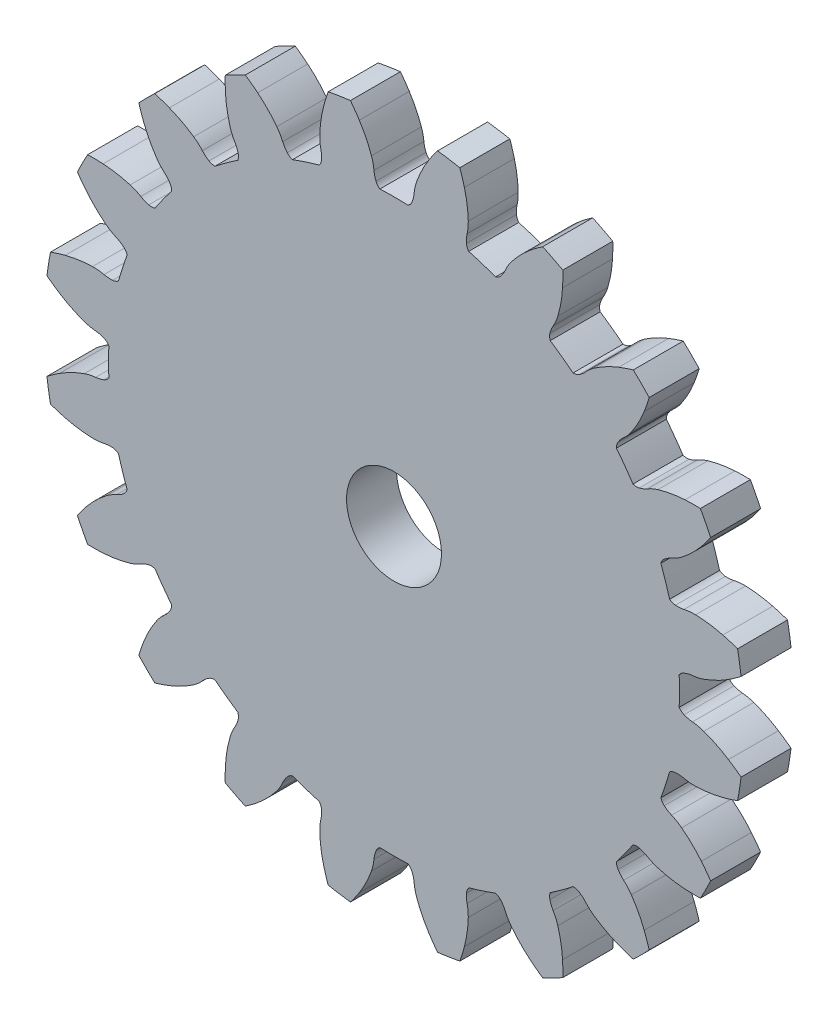
SolidWorks part; units mm, degrees
ref_plane "Front Plane" through (0, 0, 0) normal (0, 0, 1) x (1, 0, 0)
ref_plane "Top Plane" through (0, 0, 0) normal (0, 1, 0) x (1, 0, 0)
ref_plane "Right Plane" through (0, 0, 0) normal (1, 0, 0) x (0, 0, -1)
sketch "Model" plane through (0, 0, 0) normal (0, 0, 1) x (1, 0, 0)
  line L0 (-1.9599, -122.157) -> (1.9099, -120.8335)
  line L1 (1.9099, -120.8335) -> (1.9099, -119.1665)
  line L2 (1.9099, -119.1665) -> (-1.9599, -117.843)
  line L3 (-1.9599, -117.843) -> (-1.9599, -116.157)
  line L4 (-1.9599, -116.157) -> (1.9099, -114.8335)
  line L5 (1.9099, -114.8335) -> (1.9099, -113.1665)
  line L6 (1.9099, -113.1665) -> (-1.9599, -111.843)
  line L7 (-1.9599, -111.843) -> (-1.9599, -110.157)
  line L8 (-1.9599, -110.157) -> (1.9099, -108.8335)
  line L9 (1.9099, -108.8335) -> (1.9099, -107.1665)
  line L10 (1.9099, -107.1665) -> (-1.9599, -105.843)
  line L11 (-1.9599, -105.843) -> (-1.9599, -104.157)
  line L12 (-1.9599, -104.157) -> (1.9099, -102.8335)
  line L13 (1.9099, -102.8335) -> (1.9099, -101.1665)
  line L14 (1.9099, -101.1665) -> (-1.9599, -99.843)
  line L15 (-1.9599, -99.843) -> (-1.9599, -98.157)
  line L16 (-1.9599, -98.157) -> (1.9099, -96.8335)
  line L17 (1.9099, -96.8335) -> (1.9099, -95.1665)
  line L18 (1.9099, -95.1665) -> (-1.9599, -93.843)
  line L19 (-1.9599, -93.843) -> (-1.9599, -92.157)
  line L20 (-1.9599, -92.157) -> (1.9099, -90.8335)
  line L21 (1.9099, -90.8335) -> (1.9099, -89.1665)
  line L22 (1.9099, -89.1665) -> (-1.9599, -87.843)
  line L23 (-1.9599, -87.843) -> (-1.9599, -86.157)
  line L24 (-1.9599, -86.157) -> (1.9099, -84.8335)
  line L25 (1.9099, -84.8335) -> (1.9099, -83.1665)
  line L26 (1.9099, -83.1665) -> (-1.9599, -81.843)
  line L27 (-1.9599, -81.843) -> (-1.9599, -80.157)
  line L28 (-1.9599, -80.157) -> (1.9099, -78.8335)
  line L29 (1.9099, -78.8335) -> (1.9099, -77.1665)
  line L30 (1.9099, -77.1665) -> (-1.9599, -75.843)
  line L31 (-1.9599, -75.843) -> (-1.9599, -74.157)
  line L32 (-1.9599, -74.157) -> (1.9099, -72.8335)
  line L33 (1.9099, -72.8335) -> (1.9099, -71.1665)
  line L34 (1.9099, -71.1665) -> (-1.9599, -69.843)
  line L35 (-1.9599, -69.843) -> (-1.9599, -68.157)
  line L36 (-1.9599, -68.157) -> (1.9099, -66.8335)
  line L37 (1.9099, -66.8335) -> (1.9099, -65.1665)
  line L38 (1.9099, -65.1665) -> (-1.9599, -63.843)
  line L39 (-1.9599, -63.843) -> (-1.9599, -62.157)
  line L40 (-1.9599, -62.157) -> (1.9099, -60.8335)
  line L41 (1.9099, -60.8335) -> (1.9099, -59.1665)
  line L42 (1.9099, -59.1665) -> (-1.9599, -57.843)
  line L43 (-1.9599, -57.843) -> (-1.9599, -56.157)
  line L44 (-1.9599, -56.157) -> (1.9099, -54.8335)
  line L45 (1.9099, -54.8335) -> (1.9099, -53.1665)
  line L46 (1.9099, -53.1665) -> (-1.9599, -51.843)
  line L47 (-1.9599, -51.843) -> (-1.9599, -50.157)
  line L48 (-1.9599, -50.157) -> (1.9099, -48.8335)
  line L49 (1.9099, -48.8335) -> (1.9099, -47.1665)
  line L50 (1.9099, -47.1665) -> (-1.9599, -45.843)
  line L51 (-1.9599, -45.843) -> (-1.9599, -44.157)
  line L52 (-1.9599, -44.157) -> (1.9099, -42.8335)
  line L53 (1.9099, -42.8335) -> (1.9099, -41.1665)
  line L54 (1.9099, -41.1665) -> (-1.9599, -39.843)
  line L55 (-1.9599, -39.843) -> (-1.9599, -38.157)
  line L56 (-1.9599, -38.157) -> (1.9099, -36.8335)
  line L57 (1.9099, -36.8335) -> (1.9099, -35.1665)
  line L58 (1.9099, -35.1665) -> (-1.9599, -33.843)
  line L59 (-1.9599, -33.843) -> (-1.9599, -32.157)
  line L60 (-1.9599, -32.157) -> (1.9099, -30.8335)
  line L61 (1.9099, -30.8335) -> (1.9099, -29.1665)
  line L62 (1.9099, -29.1665) -> (-1.9599, -27.843)
  line L63 (-1.9599, -27.843) -> (-1.9599, -26.157)
  line L64 (-1.9599, -26.157) -> (1.9099, -24.8335)
  line L65 (1.9099, -24.8335) -> (1.9099, -23.1665)
  line L66 (1.9099, -23.1665) -> (-1.9599, -21.843)
  line L67 (-1.9599, -21.843) -> (-1.9599, -20.157)
  line L68 (-1.9599, -20.157) -> (1.9099, -18.8335)
  line L69 (1.9099, -18.8335) -> (1.9099, -17.1665)
  line L70 (1.9099, -17.1665) -> (-1.9599, -15.843)
  line L71 (-1.9599, -15.843) -> (-1.9599, -14.157)
  line L72 (-1.9599, -14.157) -> (1.9099, -12.8335)
  line L73 (1.9099, -12.8335) -> (1.9099, -11.1665)
  line L74 (1.9099, -11.1665) -> (-1.9599, -9.843)
  line L75 (-1.9599, -9.843) -> (-1.9599, -8.157)
  line L76 (-1.9599, -8.157) -> (1.9099, -6.8335)
  line L77 (1.9099, -6.8335) -> (1.9099, -5.1665)
  line L78 (1.9099, -5.1665) -> (-1.9599, -3.843)
  line L79 (-1.9599, -3.843) -> (-1.9599, -2.157)
  line L80 (-1.9599, -2.157) -> (1.9099, -0.8335)
  line L81 (1.9099, -0.8335) -> (1.9099, 0.8335)
  line L82 (1.9099, 0.8335) -> (-1.9599, 2.157)
  line L83 (-1.9599, 2.157) -> (-1.9599, 3.843)
  line L84 (-1.9599, 3.843) -> (1.9099, 5.1665)
  line L85 (1.9099, 5.1665) -> (1.9099, 6.8335)
  line L86 (1.9099, 6.8335) -> (-1.9599, 8.157)
  line L87 (-1.9599, 8.157) -> (-1.9599, 9.843)
  line L88 (-1.9599, 9.843) -> (1.9099, 11.1665)
  line L89 (1.9099, 11.1665) -> (1.9099, 12.8335)
  line L90 (1.9099, 12.8335) -> (-1.9599, 14.157)
  line L91 (-1.9599, 14.157) -> (-1.9599, 15.843)
  line L92 (-1.9599, 15.843) -> (1.9099, 17.1665)
  line L93 (1.9099, 17.1665) -> (1.9099, 18.8335)
  line L94 (1.9099, 18.8335) -> (-1.9599, 20.157)
  line L95 (-1.9599, 20.157) -> (-1.9599, 21.843)
  line L96 (-1.9599, 21.843) -> (1.9099, 23.1665)
  line L97 (1.9099, 23.1665) -> (1.9099, 24.8335)
  line L98 (1.9099, 24.8335) -> (-1.9599, 26.157)
  line L99 (-1.9599, 26.157) -> (-1.9599, 27.843)
  line L100 (-1.9599, 27.843) -> (1.9099, 29.1665)
  line L101 (1.9099, 29.1665) -> (1.9099, 30.8335)
  line L102 (1.9099, 30.8335) -> (-1.9599, 32.157)
  line L103 (-1.9599, 32.157) -> (-1.9599, 33.843)
  line L104 (-1.9599, 33.843) -> (1.9099, 35.1665)
  line L105 (1.9099, 35.1665) -> (1.9099, 36.8335)
  line L106 (1.9099, 36.8335) -> (-1.9599, 38.157)
  line L107 (-1.9599, 38.157) -> (-1.9599, 39.843)
  line L108 (-1.9599, 39.843) -> (1.9099, 41.1665)
  line L109 (1.9099, 41.1665) -> (1.9099, 42.8335)
  line L110 (1.9099, 42.8335) -> (-1.9599, 44.157)
  line L111 (-1.9599, 44.157) -> (-1.9599, 45.843)
  line L112 (-1.9599, 45.843) -> (1.9099, 47.1665)
  line L113 (1.9099, 47.1665) -> (1.9099, 48.8335)
  line L114 (1.9099, 48.8335) -> (-1.9599, 50.157)
  line L115 (-1.9599, 50.157) -> (-1.9599, 51.843)
  line L116 (-1.9599, 51.843) -> (1.9099, 53.1665)
  line L117 (1.9099, 53.1665) -> (1.9099, 54.8335)
  line L118 (1.9099, 54.8335) -> (-1.9599, 56.157)
  line L119 (-1.9599, 56.157) -> (-1.9599, 57.843)
  line L120 (-1.9599, 57.843) -> (1.9099, 59.1665)
  line L121 (1.9099, 59.1665) -> (1.9099, 60.8335)
  line L122 (1.9099, 60.8335) -> (-1.9599, 62.157)
  line L123 (-1.9599, 62.157) -> (-1.9599, 63.843)
  line L124 (-1.9599, 63.843) -> (1.9099, 65.1665)
  line L125 (1.9099, 65.1665) -> (1.9099, 66.8335)
  line L126 (1.9099, 66.8335) -> (-1.9599, 68.157)
  line L127 (-1.9599, 68.157) -> (-1.9599, 69.843)
  line L128 (-1.9599, 69.843) -> (1.9099, 71.1665)
  line L129 (1.9099, 71.1665) -> (1.9099, 72.8335)
  line L130 (1.9099, 72.8335) -> (-1.9599, 74.157)
  line L131 (-1.9599, 74.157) -> (-1.9599, 75.843)
  line L132 (-1.9599, 75.843) -> (1.9099, 77.1665)
  line L133 (1.9099, 77.1665) -> (1.9099, 78.8335)
  line L134 (1.9099, 78.8335) -> (-1.9599, 80.157)
  line L135 (-1.9599, 80.157) -> (-1.9599, 81.843)
  line L136 (-1.9599, 81.843) -> (1.9099, 83.1665)
  line L137 (1.9099, 83.1665) -> (1.9099, 84.8335)
  line L138 (1.9099, 84.8335) -> (-1.9599, 86.157)
  line L139 (-1.9599, 86.157) -> (-1.9599, 87.843)
  line L140 (-1.9599, 87.843) -> (1.9099, 89.1665)
  line L141 (1.9099, 89.1665) -> (1.9099, 90.8335)
  line L142 (1.9099, 90.8335) -> (-1.9599, 92.157)
  line L143 (-1.9599, 92.157) -> (-1.9599, 93.843)
  line L144 (-1.9599, 93.843) -> (1.9099, 95.1665)
  line L145 (1.9099, 95.1665) -> (1.9099, 96.8335)
  line L146 (1.9099, 96.8335) -> (-1.9599, 98.157)
  line L147 (-1.9599, 98.157) -> (-1.9599, 99.843)
  line L148 (-1.9599, 99.843) -> (1.9099, 101.1665)
  line L149 (1.9099, 101.1665) -> (1.9099, 102.8335)
  line L150 (1.9099, 102.8335) -> (-1.9599, 104.157)
  line L151 (-1.9599, 104.157) -> (-1.9599, 105.843)
  line L152 (-1.9599, 105.843) -> (1.9099, 107.1665)
  line L153 (1.9099, 107.1665) -> (1.9099, 108.8335)
  line L154 (1.9099, 108.8335) -> (-1.9599, 110.157)
  line L155 (-1.9599, 110.157) -> (-1.9599, 111.843)
  line L156 (-1.9599, 111.843) -> (1.9099, 113.1665)
  line L157 (1.9099, 113.1665) -> (1.9099, 114.8335)
  line L158 (1.9099, 114.8335) -> (-1.9599, 116.157)
  line L159 (-1.9599, 116.157) -> (-1.9599, 117.843)
  line L160 (-1.9599, 117.843) -> (1.9099, 119.1665)
  line L161 (1.9099, 119.1665) -> (1.9099, 120.8335)
  line L162 (1.9099, 120.8335) -> (-1.9599, 122.157)
  line L163 (-1.9599, 122.157) -> (-1.9599, 123)
  line L164 (-1.9599, 123) -> (-9.5993, 123)
  line L165 (-9.5993, 123) -> (-9.5993, -123)
  line L166 (-9.5993, -123) -> (-1.9599, -123)
  line L167 (-1.9599, -123) -> (-1.9599, -122.157)
  line L168 (-1.5377, 3.9366) -> (-1.6512, 3.2864)
  line L169 (-1.6512, 3.2864) -> (-1.7442, 2.6331)
  line L170 (-1.7442, 2.6331) -> (-1.7455, 2.6215)
  line L171 (-1.7455, 2.6215) -> (-1.7388, 2.6161)
  line L172 (-1.7388, 2.6161) -> (-1.4771, 2.4198)
  line L173 (-1.4771, 2.4198) -> (-1.2239, 2.242)
  line L174 (-1.2239, 2.242) -> (-0.9803, 2.082)
  line L175 (-0.9803, 2.082) -> (-0.7469, 1.9391)
  line L176 (-0.7469, 1.9391) -> (-0.5246, 1.8124)
  line L177 (-0.5246, 1.8124) -> (-0.3143, 1.7011)
  line L178 (-0.3143, 1.7011) -> (-0.1165, 1.6044)
  line L179 (-0.1165, 1.6044) -> (0.0679, 1.5212)
  line L180 (0.0679, 1.5212) -> (0.2383, 1.4506)
  line L181 (0.2383, 1.4506) -> (0.3942, 1.3918)
  line L182 (0.3942, 1.3918) -> (0.535, 1.3436)
  line L183 (0.535, 1.3436) -> (0.6602, 1.3051)
  line L184 (0.6602, 1.3051) -> (0.7694, 1.2753)
  line L185 (0.7694, 1.2753) -> (0.862, 1.2531)
  line L186 (0.862, 1.2531) -> (0.9379, 1.2374)
  line L187 (0.9379, 1.2374) -> (0.9966, 1.2272)
  line L188 (0.9966, 1.2272) -> (1.038, 1.2213)
  line L189 (1.038, 1.2213) -> (1.0618, 1.2187)
  line L190 (1.0618, 1.2187) -> (1.0916, 1.2164)
  line L191 (1.0916, 1.2164) -> (1.2696, 1.1958)
  line L192 (1.2696, 1.1958) -> (1.4284, 1.1659)
  line L193 (1.4284, 1.1659) -> (1.5676, 1.1277)
  line L194 (1.5676, 1.1277) -> (1.6869, 1.0826)
  line L195 (1.6869, 1.0826) -> (1.7859, 1.0316)
  line L196 (1.7859, 1.0316) -> (1.8646, 0.9761)
  line L197 (1.8646, 0.9761) -> (1.9226, 0.9172)
  line L198 (1.9226, 0.9172) -> (1.9599, 0.8563)
  line L199 (1.9599, 0.8563) -> (1.9764, 0.7945)
  line L200 (1.9764, 0.7945) -> (1.9599, 0.2692)
  line L201 (1.9599, 0.2692) -> (1.9599, -0.2692)
  line L202 (1.9599, -0.2692) -> (1.9764, -0.7945)
  line L203 (1.9764, -0.7945) -> (1.9599, -0.8563)
  line L204 (1.9599, -0.8563) -> (1.9226, -0.9172)
  line L205 (1.9226, -0.9172) -> (1.8646, -0.9761)
  line L206 (1.8646, -0.9761) -> (1.7859, -1.0316)
  line L207 (1.7859, -1.0316) -> (1.6869, -1.0826)
  line L208 (1.6869, -1.0826) -> (1.5676, -1.1277)
  line L209 (1.5676, -1.1277) -> (1.4284, -1.1659)
  line L210 (1.4284, -1.1659) -> (1.2696, -1.1958)
  line L211 (1.2696, -1.1958) -> (1.0916, -1.2164)
  line L212 (1.0916, -1.2164) -> (1.0618, -1.2187)
  line L213 (1.0618, -1.2187) -> (1.038, -1.2213)
  line L214 (1.038, -1.2213) -> (0.9966, -1.2272)
  line L215 (0.9966, -1.2272) -> (0.9379, -1.2374)
  line L216 (0.9379, -1.2374) -> (0.862, -1.2531)
  line L217 (0.862, -1.2531) -> (0.7694, -1.2753)
  line L218 (0.7694, -1.2753) -> (0.6602, -1.3051)
  line L219 (0.6602, -1.3051) -> (0.535, -1.3436)
  line L220 (0.535, -1.3436) -> (0.3942, -1.3918)
  line L221 (0.3942, -1.3918) -> (0.2383, -1.4506)
  line L222 (0.2383, -1.4506) -> (0.0679, -1.5212)
  line L223 (0.0679, -1.5212) -> (-0.1165, -1.6044)
  line L224 (-0.1165, -1.6044) -> (-0.3143, -1.7011)
  line L225 (-0.3143, -1.7011) -> (-0.5246, -1.8124)
  line L226 (-0.5246, -1.8124) -> (-0.7469, -1.9391)
  line L227 (-0.7469, -1.9391) -> (-0.9803, -2.082)
  line L228 (-0.9803, -2.082) -> (-1.2239, -2.242)
  line L229 (-1.2239, -2.242) -> (-1.4771, -2.4198)
  line L230 (-1.4771, -2.4198) -> (-1.7388, -2.6161)
  line L231 (-1.7388, -2.6161) -> (-1.7455, -2.6215)
  line L232 (-1.7455, -2.6215) -> (-1.7442, -2.6331)
  line L233 (-1.7442, -2.6331) -> (-1.6512, -3.2864)
  line L234 (-1.6512, -3.2864) -> (-1.5377, -3.9366)
  line L235 (-1.5377, -3.9366) -> (-1.5354, -3.948)
  line L236 (-1.5354, -3.948) -> (-1.5274, -3.951)
  line L237 (-1.5274, -3.951) -> (-1.2178, -4.0569)
  line L238 (-1.2178, -4.0569) -> (-0.9221, -4.1477)
  line L239 (-0.9221, -4.1477) -> (-0.6409, -4.2246)
  line L240 (-0.6409, -4.2246) -> (-0.3748, -4.2884)
  line L241 (-0.3748, -4.2884) -> (-0.1243, -4.3402)
  line L242 (-0.1243, -4.3402) -> (0.1102, -4.381)
  line L243 (0.1102, -4.381) -> (0.3281, -4.412)
  line L244 (0.3281, -4.412) -> (0.5292, -4.4341)
  line L245 (0.5292, -4.4341) -> (0.7132, -4.4485)
  line L246 (0.7132, -4.4485) -> (0.8796, -4.4563)
  line L247 (0.8796, -4.4563) -> (1.0284, -4.4586)
  line L248 (1.0284, -4.4586) -> (1.1593, -4.4565)
  line L249 (1.1593, -4.4565) -> (1.2724, -4.4511)
  line L250 (1.2724, -4.4511) -> (1.3673, -4.4436)
  line L251 (1.3673, -4.4436) -> (1.4443, -4.4351)
  line L252 (1.4443, -4.4351) -> (1.5034, -4.4267)
  line L253 (1.5034, -4.4267) -> (1.5445, -4.4195)
  line L254 (1.5445, -4.4195) -> (1.568, -4.4146)
  line L255 (1.568, -4.4146) -> (1.5971, -4.4076)
  line L256 (1.5971, -4.4076) -> (1.7727, -4.3722)
  line L257 (1.7727, -4.3722) -> (1.933, -4.3516)
  line L258 (1.933, -4.3516) -> (2.0771, -4.3448)
  line L259 (2.0771, -4.3448) -> (2.2045, -4.3509)
  line L260 (2.2045, -4.3509) -> (2.3145, -4.3688)
  line L261 (2.3145, -4.3688) -> (2.4064, -4.3973)
  line L262 (2.4064, -4.3973) -> (2.4798, -4.4353)
  line L263 (2.4798, -4.4353) -> (2.5341, -4.4818)
  line L264 (2.5341, -4.4818) -> (2.5689, -4.5354)
  line L265 (2.5689, -4.5354) -> (2.7155, -5.0401)
  line L266 (2.7155, -5.0401) -> (2.8819, -5.5522)
  line L267 (2.8819, -5.5522) -> (3.0599, -6.0467)
  line L268 (3.0599, -6.0467) -> (3.0633, -6.1105)
  line L269 (3.0633, -6.1105) -> (3.0467, -6.18)
  line L270 (3.0467, -6.18) -> (3.0097, -6.2539)
  line L271 (3.0097, -6.2539) -> (2.9521, -6.331)
  line L272 (2.9521, -6.331) -> (2.8736, -6.4101)
  line L273 (2.8736, -6.4101) -> (2.7741, -6.4899)
  line L274 (2.7741, -6.4899) -> (2.6535, -6.5692)
  line L275 (2.6535, -6.5692) -> (2.5118, -6.6468)
  line L276 (2.5118, -6.6468) -> (2.3488, -6.7213)
  line L277 (2.3488, -6.7213) -> (2.3212, -6.7327)
  line L278 (2.3212, -6.7327) -> (2.2993, -6.7426)
  line L279 (2.2993, -6.7426) -> (2.2618, -6.761)
  line L280 (2.2618, -6.761) -> (2.2091, -6.7888)
  line L281 (2.2091, -6.7888) -> (2.1418, -6.8272)
  line L282 (2.1418, -6.8272) -> (2.0605, -6.877)
  line L283 (2.0605, -6.877) -> (1.966, -6.939)
  line L284 (1.966, -6.939) -> (1.8588, -7.0143)
  line L285 (1.8588, -7.0143) -> (1.7398, -7.1036)
  line L286 (1.7398, -7.1036) -> (1.6097, -7.2078)
  line L287 (1.6097, -7.2078) -> (1.4694, -7.3275)
  line L288 (1.4694, -7.3275) -> (1.3197, -7.4636)
  line L289 (1.3197, -7.4636) -> (1.1616, -7.6168)
  line L290 (1.1616, -7.6168) -> (0.9959, -7.7876)
  line L291 (0.9959, -7.7876) -> (0.8236, -7.9768)
  line L292 (0.8236, -7.9768) -> (0.6459, -8.1848)
  line L293 (0.6459, -8.1848) -> (0.4635, -8.4123)
  line L294 (0.4635, -8.4123) -> (0.2777, -8.6596)
  line L295 (0.2777, -8.6596) -> (0.0895, -8.9272)
  line L296 (0.0895, -8.9272) -> (0.0848, -8.9344)
  line L297 (0.0848, -8.9344) -> (0.0896, -8.945)
  line L298 (0.0896, -8.945) -> (0.3799, -9.5376)
  line L299 (0.3799, -9.5376) -> (0.6887, -10.1209)
  line L300 (0.6887, -10.1209) -> (0.6945, -10.131)
  line L301 (0.6945, -10.131) -> (0.7031, -10.1314)
  line L302 (0.7031, -10.1314) -> (1.0302, -10.1364)
  line L303 (1.0302, -10.1364) -> (1.3395, -10.1315)
  line L304 (1.3395, -10.1315) -> (1.6307, -10.1177)
  line L305 (1.6307, -10.1177) -> (1.9035, -10.0961)
  line L306 (1.9035, -10.0961) -> (2.1578, -10.0679)
  line L307 (2.1578, -10.0679) -> (2.3934, -10.0343)
  line L308 (2.3934, -10.0343) -> (2.6102, -9.9964)
  line L309 (2.6102, -9.9964) -> (2.8083, -9.9553)
  line L310 (2.8083, -9.9553) -> (2.9877, -9.9122)
  line L311 (2.9877, -9.9122) -> (3.1484, -9.8682)
  line L312 (3.1484, -9.8682) -> (3.2906, -9.8244)
  line L313 (3.2906, -9.8244) -> (3.4145, -9.7819)
  line L314 (3.4145, -9.7819) -> (3.5203, -9.7419)
  line L315 (3.5203, -9.7419) -> (3.6083, -9.7054)
  line L316 (3.6083, -9.7054) -> (3.6789, -9.6735)
  line L317 (3.6789, -9.6735) -> (3.7324, -9.6473)
  line L318 (3.7324, -9.6473) -> (3.7694, -9.6277)
  line L319 (3.7694, -9.6277) -> (3.7902, -9.6158)
  line L320 (3.7902, -9.6158) -> (3.8157, -9.6002)
  line L321 (3.8157, -9.6002) -> (3.9718, -9.5122)
  line L322 (3.9718, -9.5122) -> (4.1178, -9.4431)
  line L323 (4.1178, -9.4431) -> (4.2529, -9.3921)
  line L324 (4.2529, -9.3921) -> (4.3759, -9.3585)
  line L325 (4.3759, -9.3585) -> (4.486, -9.3415)
  line L326 (4.486, -9.3415) -> (4.5822, -9.3402)
  line L327 (4.5822, -9.3402) -> (4.6638, -9.3538)
  line L328 (4.6638, -9.3538) -> (4.7297, -9.3811)
  line L329 (4.7297, -9.3811) -> (4.7794, -9.4214)
  line L330 (4.7794, -9.4214) -> (5.0748, -9.8561)
  line L331 (5.0748, -9.8561) -> (5.3913, -10.2917)
  line L332 (5.3913, -10.2917) -> (5.7134, -10.707)
  line L333 (5.7134, -10.707) -> (5.7364, -10.7667)
  line L334 (5.7364, -10.7667) -> (5.742, -10.8379)
  line L335 (5.742, -10.8379) -> (5.7297, -10.9196)
  line L336 (5.7297, -10.9196) -> (5.6987, -11.0107)
  line L337 (5.6987, -11.0107) -> (5.6485, -11.1102)
  line L338 (5.6485, -11.1102) -> (5.5786, -11.2168)
  line L339 (5.5786, -11.2168) -> (5.4884, -11.3295)
  line L340 (5.4884, -11.3295) -> (5.3775, -11.447)
  line L341 (5.3775, -11.447) -> (5.2456, -11.5683)
  line L342 (5.2456, -11.5683) -> (5.2228, -11.5877)
  line L343 (5.2228, -11.5877) -> (5.2051, -11.6038)
  line L344 (5.2051, -11.6038) -> (5.1751, -11.6329)
  line L345 (5.1751, -11.6329) -> (5.1336, -11.6757)
  line L346 (5.1336, -11.6757) -> (5.0815, -11.733)
  line L347 (5.0815, -11.733) -> (5.0195, -11.8054)
  line L348 (5.0195, -11.8054) -> (4.9488, -11.8937)
  line L349 (4.9488, -11.8937) -> (4.8701, -11.9984)
  line L350 (4.8701, -11.9984) -> (4.7845, -12.1201)
  line L351 (4.7845, -12.1201) -> (4.693, -12.2594)
  line L352 (4.693, -12.2594) -> (4.5965, -12.4166)
  line L353 (4.5965, -12.4166) -> (4.4962, -12.5923)
  line L354 (4.4962, -12.5923) -> (4.3932, -12.7868)
  line L355 (4.3932, -12.7868) -> (4.2884, -13.0005)
  line L356 (4.2884, -13.0005) -> (4.1831, -13.2337)
  line L357 (4.1831, -13.2337) -> (4.0782, -13.4865)
  line L358 (4.0782, -13.4865) -> (3.9751, -13.7591)
  line L359 (3.9751, -13.7591) -> (3.8748, -14.0517)
  line L360 (3.8748, -14.0517) -> (3.7785, -14.3644)
  line L361 (3.7785, -14.3644) -> (3.7763, -14.3727)
  line L362 (3.7763, -14.3727) -> (3.7841, -14.3813)
  line L363 (3.7841, -14.3813) -> (4.2434, -14.8552)
  line L364 (4.2434, -14.8552) -> (4.7173, -15.3145)
  line L365 (4.7173, -15.3145) -> (4.7259, -15.3223)
  line L366 (4.7259, -15.3223) -> (4.7342, -15.3201)
  line L367 (4.7342, -15.3201) -> (5.0469, -15.2238)
  line L368 (5.0469, -15.2238) -> (5.3395, -15.1235)
  line L369 (5.3395, -15.1235) -> (5.6121, -15.0203)
  line L370 (5.6121, -15.0203) -> (5.8649, -14.9155)
  line L371 (5.8649, -14.9155) -> (6.0981, -14.8102)
  line L372 (6.0981, -14.8102) -> (6.3117, -14.7054)
  line L373 (6.3117, -14.7054) -> (6.5063, -14.6023)
  line L374 (6.5063, -14.6023) -> (6.682, -14.5021)
  line L375 (6.682, -14.5021) -> (6.8392, -14.4056)
  line L376 (6.8392, -14.4056) -> (6.9785, -14.3141)
  line L377 (6.9785, -14.3141) -> (7.1002, -14.2285)
  line L378 (7.1002, -14.2285) -> (7.2049, -14.1498)
  line L379 (7.2049, -14.1498) -> (7.2932, -14.0791)
  line L380 (7.2932, -14.0791) -> (7.3656, -14.0171)
  line L381 (7.3656, -14.0171) -> (7.4229, -13.965)
  line L382 (7.4229, -13.965) -> (7.4657, -13.9235)
  line L383 (7.4657, -13.9235) -> (7.4948, -13.8935)
  line L384 (7.4948, -13.8935) -> (7.5109, -13.8758)
  line L385 (7.5109, -13.8758) -> (7.5303, -13.853)
  line L386 (7.5303, -13.853) -> (7.6515, -13.7211)
  line L387 (7.6515, -13.7211) -> (7.7691, -13.6102)
  line L388 (7.7691, -13.6102) -> (7.8818, -13.52)
  line L389 (7.8818, -13.52) -> (7.9884, -13.4501)
  line L390 (7.9884, -13.4501) -> (8.0879, -13.3999)
  line L391 (8.0879, -13.3999) -> (8.179, -13.3689)
  line L392 (8.179, -13.3689) -> (8.2607, -13.3566)
  line L393 (8.2607, -13.3566) -> (8.3319, -13.3622)
  line L394 (8.3319, -13.3622) -> (8.3916, -13.3852)
  line L395 (8.3916, -13.3852) -> (8.8069, -13.7073)
  line L396 (8.8069, -13.7073) -> (9.2425, -14.0238)
  line L397 (9.2425, -14.0238) -> (9.6772, -14.3192)
  line L398 (9.6772, -14.3192) -> (9.7175, -14.3688)
  line L399 (9.7175, -14.3688) -> (9.7448, -14.4348)
  line L400 (9.7448, -14.4348) -> (9.7584, -14.5164)
  line L401 (9.7584, -14.5164) -> (9.7571, -14.6126)
  line L402 (9.7571, -14.6126) -> (9.7401, -14.7227)
  line L403 (9.7401, -14.7227) -> (9.7065, -14.8457)
  line L404 (9.7065, -14.8457) -> (9.6555, -14.9808)
  line L405 (9.6555, -14.9808) -> (9.5864, -15.1268)
  line L406 (9.5864, -15.1268) -> (9.4984, -15.2829)
  line L407 (9.4984, -15.2829) -> (9.4828, -15.3084)
  line L408 (9.4828, -15.3084) -> (9.4709, -15.3292)
  line L409 (9.4709, -15.3292) -> (9.4513, -15.3661)
  line L410 (9.4513, -15.3661) -> (9.4251, -15.4197)
  line L411 (9.4251, -15.4197) -> (9.3932, -15.4903)
  line L412 (9.3932, -15.4903) -> (9.3567, -15.5783)
  line L413 (9.3567, -15.5783) -> (9.3167, -15.6841)
  line L414 (9.3167, -15.6841) -> (9.2742, -15.808)
  line L415 (9.2742, -15.808) -> (9.2304, -15.9502)
  line L416 (9.2304, -15.9502) -> (9.1864, -16.1109)
  line L417 (9.1864, -16.1109) -> (9.1433, -16.2903)
  line L418 (9.1433, -16.2903) -> (9.1022, -16.4884)
  line L419 (9.1022, -16.4884) -> (9.0643, -16.7052)
  line L420 (9.0643, -16.7052) -> (9.0307, -16.9408)
  line L421 (9.0307, -16.9408) -> (9.0025, -17.1951)
  line L422 (9.0025, -17.1951) -> (8.9809, -17.4679)
  line L423 (8.9809, -17.4679) -> (8.9671, -17.7591)
  line L424 (8.9671, -17.7591) -> (8.9622, -18.0684)
  line L425 (8.9622, -18.0684) -> (8.9672, -18.3955)
  line L426 (8.9672, -18.3955) -> (8.9676, -18.4041)
  line L427 (8.9676, -18.4041) -> (8.9777, -18.4098)
  line L428 (8.9777, -18.4098) -> (9.561, -18.7187)
  line L429 (9.561, -18.7187) -> (10.1536, -19.009)
  line L430 (10.1536, -19.009) -> (10.1642, -19.0138)
  line L431 (10.1642, -19.0138) -> (10.1714, -19.0091)
  line L432 (10.1714, -19.0091) -> (10.439, -18.8209)
  line L433 (10.439, -18.8209) -> (10.6863, -18.6351)
  line L434 (10.6863, -18.6351) -> (10.9138, -18.4527)
  line L435 (10.9138, -18.4527) -> (11.1218, -18.2749)
  line L436 (11.1218, -18.2749) -> (11.311, -18.1027)
  line L437 (11.311, -18.1027) -> (11.4818, -17.937)
  line L438 (11.4818, -17.937) -> (11.635, -17.7789)
  line L439 (11.635, -17.7789) -> (11.7711, -17.6292)
  line L440 (11.7711, -17.6292) -> (11.8908, -17.4889)
  line L441 (11.8908, -17.4889) -> (11.995, -17.3588)
  line L442 (11.995, -17.3588) -> (12.0843, -17.2398)
  line L443 (12.0843, -17.2398) -> (12.1596, -17.1326)
  line L444 (12.1596, -17.1326) -> (12.2216, -17.038)
  line L445 (12.2216, -17.038) -> (12.2714, -16.9568)
  line L446 (12.2714, -16.9568) -> (12.3098, -16.8895)
  line L447 (12.3098, -16.8895) -> (12.3376, -16.8368)
  line L448 (12.3376, -16.8368) -> (12.356, -16.7993)
  line L449 (12.356, -16.7993) -> (12.3659, -16.7774)
  line L450 (12.3659, -16.7774) -> (12.3773, -16.7498)
  line L451 (12.3773, -16.7498) -> (12.4518, -16.5868)
  line L452 (12.4518, -16.5868) -> (12.5294, -16.4451)
  line L453 (12.5294, -16.4451) -> (12.6087, -16.3245)
  line L454 (12.6087, -16.3245) -> (12.6885, -16.225)
  line L455 (12.6885, -16.225) -> (12.7676, -16.1465)
  line L456 (12.7676, -16.1465) -> (12.8447, -16.0889)
  line L457 (12.8447, -16.0889) -> (12.9186, -16.0519)
  line L458 (12.9186, -16.0519) -> (12.9881, -16.0353)
  line L459 (12.9881, -16.0353) -> (13.0519, -16.0387)
  line L460 (13.0519, -16.0387) -> (13.5464, -16.2167)
  line L461 (13.5464, -16.2167) -> (14.0585, -16.3831)
  line L462 (14.0585, -16.3831) -> (14.5632, -16.5297)
  line L463 (14.5632, -16.5297) -> (14.6168, -16.5645)
  line L464 (14.6168, -16.5645) -> (14.6633, -16.6188)
  line L465 (14.6633, -16.6188) -> (14.7013, -16.6922)
  line L466 (14.7013, -16.6922) -> (14.7298, -16.7841)
  line L467 (14.7298, -16.7841) -> (14.7477, -16.8941)
  line L468 (14.7477, -16.8941) -> (14.7538, -17.0214)
  line L469 (14.7538, -17.0214) -> (14.747, -17.1656)
  line L470 (14.747, -17.1656) -> (14.7264, -17.3259)
  line L471 (14.7264, -17.3259) -> (14.691, -17.5015)
  line L472 (14.691, -17.5015) -> (14.684, -17.5306)
  line L473 (14.684, -17.5306) -> (14.6791, -17.5541)
  line L474 (14.6791, -17.5541) -> (14.6719, -17.5952)
  line L475 (14.6719, -17.5952) -> (14.6635, -17.6543)
  line L476 (14.6635, -17.6543) -> (14.655, -17.7312)
  line L477 (14.655, -17.7312) -> (14.6475, -17.8262)
  line L478 (14.6475, -17.8262) -> (14.6421, -17.9392)
  line L479 (14.6421, -17.9392) -> (14.64, -18.0702)
  line L480 (14.64, -18.0702) -> (14.6423, -18.219)
  line L481 (14.6423, -18.219) -> (14.6501, -18.3854)
  line L482 (14.6501, -18.3854) -> (14.6645, -18.5693)
  line L483 (14.6645, -18.5693) -> (14.6866, -18.7704)
  line L484 (14.6866, -18.7704) -> (14.7176, -18.9884)
  line L485 (14.7176, -18.9884) -> (14.7584, -19.2229)
  line L486 (14.7584, -19.2229) -> (14.8102, -19.4734)
  line L487 (14.8102, -19.4734) -> (14.874, -19.7395)
  line L488 (14.874, -19.7395) -> (14.9508, -20.0207)
  line L489 (14.9508, -20.0207) -> (15.0417, -20.3164)
  line L490 (15.0417, -20.3164) -> (15.1476, -20.6259)
  line L491 (15.1476, -20.6259) -> (15.1506, -20.634)
  line L492 (15.1506, -20.634) -> (15.162, -20.6363)
  line L493 (15.162, -20.6363) -> (15.8121, -20.7498)
  line L494 (15.8121, -20.7498) -> (16.4655, -20.8428)
  line L495 (16.4655, -20.8428) -> (16.4771, -20.8441)
  line L496 (16.4771, -20.8441) -> (16.4825, -20.8374)
  line L497 (16.4825, -20.8374) -> (16.6788, -20.5757)
  line L498 (16.6788, -20.5757) -> (16.8566, -20.3225)
  line L499 (16.8566, -20.3225) -> (17.0166, -20.0789)
  line L500 (17.0166, -20.0789) -> (17.1595, -19.8455)
  line L501 (17.1595, -19.8455) -> (17.2862, -19.6232)
  line L502 (17.2862, -19.6232) -> (17.3974, -19.4129)
  line L503 (17.3974, -19.4129) -> (17.4942, -19.2151)
  line L504 (17.4942, -19.2151) -> (17.5774, -19.0307)
  line L505 (17.5774, -19.0307) -> (17.648, -18.8603)
  line L506 (17.648, -18.8603) -> (17.7068, -18.7044)
  line L507 (17.7068, -18.7044) -> (17.755, -18.5636)
  line L508 (17.755, -18.5636) -> (17.7935, -18.4384)
  line L509 (17.7935, -18.4384) -> (17.8233, -18.3292)
  line L510 (17.8233, -18.3292) -> (17.8455, -18.2366)
  line L511 (17.8455, -18.2366) -> (17.8612, -18.1607)
  line L512 (17.8612, -18.1607) -> (17.8714, -18.102)
  line L513 (17.8714, -18.102) -> (17.8773, -18.0606)
  line L514 (17.8773, -18.0606) -> (17.8799, -18.0368)
  line L515 (17.8799, -18.0368) -> (17.8822, -18.007)
  line L516 (17.8822, -18.007) -> (17.9028, -17.829)
  line L517 (17.9028, -17.829) -> (17.9327, -17.6702)
  line L518 (17.9327, -17.6702) -> (17.9709, -17.531)
  line L519 (17.9709, -17.531) -> (18.016, -17.4117)
  line L520 (18.016, -17.4117) -> (18.067, -17.3127)
  line L521 (18.067, -17.3127) -> (18.1225, -17.234)
  line L522 (18.1225, -17.234) -> (18.1814, -17.176)
  line L523 (18.1814, -17.176) -> (18.2423, -17.1387)
  line L524 (18.2423, -17.1387) -> (18.3041, -17.1222)
  line L525 (18.3041, -17.1222) -> (18.8294, -17.1387)
  line L526 (18.8294, -17.1387) -> (19.3678, -17.1387)
  line L527 (19.3678, -17.1387) -> (19.8931, -17.1222)
  line L528 (19.8931, -17.1222) -> (19.9549, -17.1387)
  line L529 (19.9549, -17.1387) -> (20.0158, -17.176)
  line L530 (20.0158, -17.176) -> (20.0747, -17.234)
  line L531 (20.0747, -17.234) -> (20.1302, -17.3127)
  line L532 (20.1302, -17.3127) -> (20.1812, -17.4117)
  line L533 (20.1812, -17.4117) -> (20.2263, -17.531)
  line L534 (20.2263, -17.531) -> (20.2645, -17.6702)
  line L535 (20.2645, -17.6702) -> (20.2944, -17.829)
  line L536 (20.2944, -17.829) -> (20.315, -18.007)
  line L537 (20.315, -18.007) -> (20.3173, -18.0368)
  line L538 (20.3173, -18.0368) -> (20.3199, -18.0606)
  line L539 (20.3199, -18.0606) -> (20.3258, -18.102)
  line L540 (20.3258, -18.102) -> (20.336, -18.1607)
  line L541 (20.336, -18.1607) -> (20.3517, -18.2366)
  line L542 (20.3517, -18.2366) -> (20.3739, -18.3292)
  line L543 (20.3739, -18.3292) -> (20.4037, -18.4384)
  line L544 (20.4037, -18.4384) -> (20.4422, -18.5636)
  line L545 (20.4422, -18.5636) -> (20.4904, -18.7044)
  line L546 (20.4904, -18.7044) -> (20.5492, -18.8603)
  line L547 (20.5492, -18.8603) -> (20.6198, -19.0307)
  line L548 (20.6198, -19.0307) -> (20.703, -19.2151)
  line L549 (20.703, -19.2151) -> (20.7997, -19.4129)
  line L550 (20.7997, -19.4129) -> (20.911, -19.6232)
  line L551 (20.911, -19.6232) -> (21.0377, -19.8455)
  line L552 (21.0377, -19.8455) -> (21.1806, -20.0789)
  line L553 (21.1806, -20.0789) -> (21.3406, -20.3225)
  line L554 (21.3406, -20.3225) -> (21.5184, -20.5757)
  line L555 (21.5184, -20.5757) -> (21.7147, -20.8374)
  line L556 (21.7147, -20.8374) -> (21.7201, -20.8441)
  line L557 (21.7201, -20.8441) -> (21.7317, -20.8428)
  line L558 (21.7317, -20.8428) -> (22.385, -20.7498)
  line L559 (22.385, -20.7498) -> (23.0352, -20.6363)
  line L560 (23.0352, -20.6363) -> (23.0466, -20.634)
  line L561 (23.0466, -20.634) -> (23.0496, -20.6259)
  line L562 (23.0496, -20.6259) -> (23.1555, -20.3164)
  line L563 (23.1555, -20.3164) -> (23.2463, -20.0207)
  line L564 (23.2463, -20.0207) -> (23.3232, -19.7395)
  line L565 (23.3232, -19.7395) -> (23.387, -19.4734)
  line L566 (23.387, -19.4734) -> (23.4388, -19.2229)
  line L567 (23.4388, -19.2229) -> (23.4796, -18.9884)
  line L568 (23.4796, -18.9884) -> (23.5106, -18.7704)
  line L569 (23.5106, -18.7704) -> (23.5327, -18.5693)
  line L570 (23.5327, -18.5693) -> (23.5471, -18.3854)
  line L571 (23.5471, -18.3854) -> (23.5549, -18.219)
  line L572 (23.5549, -18.219) -> (23.5572, -18.0702)
  line L573 (23.5572, -18.0702) -> (23.5551, -17.9392)
  line L574 (23.5551, -17.9392) -> (23.5497, -17.8262)
  line L575 (23.5497, -17.8262) -> (23.5422, -17.7312)
  line L576 (23.5422, -17.7312) -> (23.5337, -17.6543)
  line L577 (23.5337, -17.6543) -> (23.5253, -17.5952)
  line L578 (23.5253, -17.5952) -> (23.5181, -17.5541)
  line L579 (23.5181, -17.5541) -> (23.5132, -17.5306)
  line L580 (23.5132, -17.5306) -> (23.5062, -17.5015)
  line L581 (23.5062, -17.5015) -> (23.4708, -17.3259)
  line L582 (23.4708, -17.3259) -> (23.4502, -17.1656)
  line L583 (23.4502, -17.1656) -> (23.4434, -17.0214)
  line L584 (23.4434, -17.0214) -> (23.4495, -16.8941)
  line L585 (23.4495, -16.8941) -> (23.4674, -16.7841)
  line L586 (23.4674, -16.7841) -> (23.4959, -16.6922)
  line L587 (23.4959, -16.6922) -> (23.5339, -16.6188)
  line L588 (23.5339, -16.6188) -> (23.5804, -16.5645)
  line L589 (23.5804, -16.5645) -> (23.634, -16.5297)
  line L590 (23.634, -16.5297) -> (24.1387, -16.3831)
  line L591 (24.1387, -16.3831) -> (24.6508, -16.2167)
  line L592 (24.6508, -16.2167) -> (25.1453, -16.0387)
  line L593 (25.1453, -16.0387) -> (25.2091, -16.0353)
  line L594 (25.2091, -16.0353) -> (25.2786, -16.0519)
  line L595 (25.2786, -16.0519) -> (25.3525, -16.0889)
  line L596 (25.3525, -16.0889) -> (25.4296, -16.1465)
  line L597 (25.4296, -16.1465) -> (25.5087, -16.225)
  line L598 (25.5087, -16.225) -> (25.5885, -16.3245)
  line L599 (25.5885, -16.3245) -> (25.6678, -16.4451)
  line L600 (25.6678, -16.4451) -> (25.7453, -16.5868)
  line L601 (25.7453, -16.5868) -> (25.8199, -16.7498)
  line L602 (25.8199, -16.7498) -> (25.8313, -16.7774)
  line L603 (25.8313, -16.7774) -> (25.8412, -16.7993)
  line L604 (25.8412, -16.7993) -> (25.8595, -16.8368)
  line L605 (25.8595, -16.8368) -> (25.8874, -16.8895)
  line L606 (25.8874, -16.8895) -> (25.9258, -16.9568)
  line L607 (25.9258, -16.9568) -> (25.9755, -17.038)
  line L608 (25.9755, -17.038) -> (26.0376, -17.1326)
  line L609 (26.0376, -17.1326) -> (26.1129, -17.2398)
  line L610 (26.1129, -17.2398) -> (26.2022, -17.3588)
  line L611 (26.2022, -17.3588) -> (26.3064, -17.4889)
  line L612 (26.3064, -17.4889) -> (26.4261, -17.6292)
  line L613 (26.4261, -17.6292) -> (26.5622, -17.7789)
  line L614 (26.5622, -17.7789) -> (26.7154, -17.937)
  line L615 (26.7154, -17.937) -> (26.8862, -18.1027)
  line L616 (26.8862, -18.1027) -> (27.0754, -18.2749)
  line L617 (27.0754, -18.2749) -> (27.2834, -18.4527)
  line L618 (27.2834, -18.4527) -> (27.5109, -18.6351)
  line L619 (27.5109, -18.6351) -> (27.7582, -18.8209)
  line L620 (27.7582, -18.8209) -> (28.0258, -19.0091)
  line L621 (28.0258, -19.0091) -> (28.033, -19.0138)
  line L622 (28.033, -19.0138) -> (28.0436, -19.009)
  line L623 (28.0436, -19.009) -> (28.6362, -18.7187)
  line L624 (28.6362, -18.7187) -> (29.2195, -18.4098)
  line L625 (29.2195, -18.4098) -> (29.2296, -18.4041)
  line L626 (29.2296, -18.4041) -> (29.23, -18.3955)
  line L627 (29.23, -18.3955) -> (29.235, -18.0684)
  line L628 (29.235, -18.0684) -> (29.2301, -17.7591)
  line L629 (29.2301, -17.7591) -> (29.2162, -17.4679)
  line L630 (29.2162, -17.4679) -> (29.1947, -17.1951)
  line L631 (29.1947, -17.1951) -> (29.1665, -16.9408)
  line L632 (29.1665, -16.9408) -> (29.1329, -16.7052)
  line L633 (29.1329, -16.7052) -> (29.095, -16.4884)
  line L634 (29.095, -16.4884) -> (29.0539, -16.2903)
  line L635 (29.0539, -16.2903) -> (29.0108, -16.1109)
  line L636 (29.0108, -16.1109) -> (28.9668, -15.9502)
  line L637 (28.9668, -15.9502) -> (28.923, -15.808)
  line L638 (28.923, -15.808) -> (28.8805, -15.6841)
  line L639 (28.8805, -15.6841) -> (28.8405, -15.5783)
  line L640 (28.8405, -15.5783) -> (28.804, -15.4903)
  line L641 (28.804, -15.4903) -> (28.7721, -15.4197)
  line L642 (28.7721, -15.4197) -> (28.7459, -15.3661)
  line L643 (28.7459, -15.3661) -> (28.7263, -15.3292)
  line L644 (28.7263, -15.3292) -> (28.7144, -15.3084)
  line L645 (28.7144, -15.3084) -> (28.6988, -15.2829)
  line L646 (28.6988, -15.2829) -> (28.6108, -15.1268)
  line L647 (28.6108, -15.1268) -> (28.5416, -14.9808)
  line L648 (28.5416, -14.9808) -> (28.4907, -14.8457)
  line L649 (28.4907, -14.8457) -> (28.4571, -14.7227)
  line L650 (28.4571, -14.7227) -> (28.4401, -14.6126)
  line L651 (28.4401, -14.6126) -> (28.4388, -14.5164)
  line L652 (28.4388, -14.5164) -> (28.4523, -14.4348)
  line L653 (28.4523, -14.4348) -> (28.4797, -14.3688)
  line L654 (28.4797, -14.3688) -> (28.52, -14.3192)
  line L655 (28.52, -14.3192) -> (28.9547, -14.0238)
  line L656 (28.9547, -14.0238) -> (29.3903, -13.7073)
  line L657 (29.3903, -13.7073) -> (29.8056, -13.3852)
  line L658 (29.8056, -13.3852) -> (29.8652, -13.3622)
  line L659 (29.8652, -13.3622) -> (29.9365, -13.3566)
  line L660 (29.9365, -13.3566) -> (30.0182, -13.3689)
  line L661 (30.0182, -13.3689) -> (30.1093, -13.3999)
  line L662 (30.1093, -13.3999) -> (30.2088, -13.4501)
  line L663 (30.2088, -13.4501) -> (30.3154, -13.52)
  line L664 (30.3154, -13.52) -> (30.4281, -13.6102)
  line L665 (30.4281, -13.6102) -> (30.5456, -13.7211)
  line L666 (30.5456, -13.7211) -> (30.6669, -13.853)
  line L667 (30.6669, -13.853) -> (30.6863, -13.8758)
  line L668 (30.6863, -13.8758) -> (30.7024, -13.8935)
  line L669 (30.7024, -13.8935) -> (30.7315, -13.9235)
  line L670 (30.7315, -13.9235) -> (30.7743, -13.965)
  line L671 (30.7743, -13.965) -> (30.8316, -14.0171)
  line L672 (30.8316, -14.0171) -> (30.904, -14.0791)
  line L673 (30.904, -14.0791) -> (30.9923, -14.1498)
  line L674 (30.9923, -14.1498) -> (31.097, -14.2285)
  line L675 (31.097, -14.2285) -> (31.2187, -14.3141)
  line L676 (31.2187, -14.3141) -> (31.3579, -14.4056)
  line L677 (31.3579, -14.4056) -> (31.5152, -14.5021)
  line L678 (31.5152, -14.5021) -> (31.6909, -14.6023)
  line L679 (31.6909, -14.6023) -> (31.8854, -14.7054)
  line L680 (31.8854, -14.7054) -> (32.0991, -14.8102)
  line L681 (32.0991, -14.8102) -> (32.3323, -14.9155)
  line L682 (32.3323, -14.9155) -> (32.585, -15.0203)
  line L683 (32.585, -15.0203) -> (32.8577, -15.1235)
  line L684 (32.8577, -15.1235) -> (33.1503, -15.2238)
  line L685 (33.1503, -15.2238) -> (33.463, -15.3201)
  line L686 (33.463, -15.3201) -> (33.4713, -15.3223)
  line L687 (33.4713, -15.3223) -> (33.4799, -15.3145)
  line L688 (33.4799, -15.3145) -> (33.9538, -14.8552)
  line L689 (33.9538, -14.8552) -> (34.4131, -14.3813)
  line L690 (34.4131, -14.3813) -> (34.4209, -14.3727)
  line L691 (34.4209, -14.3727) -> (34.4187, -14.3644)
  line L692 (34.4187, -14.3644) -> (34.3224, -14.0517)
  line L693 (34.3224, -14.0517) -> (34.2221, -13.7591)
  line L694 (34.2221, -13.7591) -> (34.1189, -13.4865)
  line L695 (34.1189, -13.4865) -> (34.0141, -13.2337)
  line L696 (34.0141, -13.2337) -> (33.9088, -13.0005)
  line L697 (33.9088, -13.0005) -> (33.804, -12.7868)
  line L698 (33.804, -12.7868) -> (33.7009, -12.5923)
  line L699 (33.7009, -12.5923) -> (33.6006, -12.4166)
  line L700 (33.6006, -12.4166) -> (33.5042, -12.2594)
  line L701 (33.5042, -12.2594) -> (33.4127, -12.1201)
  line L702 (33.4127, -12.1201) -> (33.3271, -11.9984)
  line L703 (33.3271, -11.9984) -> (33.2484, -11.8937)
  line L704 (33.2484, -11.8937) -> (33.1776, -11.8054)
  line L705 (33.1776, -11.8054) -> (33.1157, -11.733)
  line L706 (33.1157, -11.733) -> (33.0636, -11.6757)
  line L707 (33.0636, -11.6757) -> (33.0221, -11.6329)
  line L708 (33.0221, -11.6329) -> (32.9921, -11.6038)
  line L709 (32.9921, -11.6038) -> (32.9744, -11.5877)
  line L710 (32.9744, -11.5877) -> (32.9516, -11.5683)
  line L711 (32.9516, -11.5683) -> (32.8196, -11.447)
  line L712 (32.8196, -11.447) -> (32.7088, -11.3295)
  line L713 (32.7088, -11.3295) -> (32.6186, -11.2168)
  line L714 (32.6186, -11.2168) -> (32.5486, -11.1102)
  line L715 (32.5486, -11.1102) -> (32.4985, -11.0107)
  line L716 (32.4985, -11.0107) -> (32.4675, -10.9196)
  line L717 (32.4675, -10.9196) -> (32.4551, -10.8379)
  line L718 (32.4551, -10.8379) -> (32.4608, -10.7667)
  line L719 (32.4608, -10.7667) -> (32.4838, -10.707)
  line L720 (32.4838, -10.707) -> (32.8059, -10.2917)
  line L721 (32.8059, -10.2917) -> (33.1224, -9.8561)
  line L722 (33.1224, -9.8561) -> (33.4178, -9.4214)
  line L723 (33.4178, -9.4214) -> (33.4674, -9.3811)
  line L724 (33.4674, -9.3811) -> (33.5334, -9.3538)
  line L725 (33.5334, -9.3538) -> (33.6149, -9.3402)
  line L726 (33.6149, -9.3402) -> (33.7112, -9.3415)
  line L727 (33.7112, -9.3415) -> (33.8213, -9.3585)
  line L728 (33.8213, -9.3585) -> (33.9443, -9.3921)
  line L729 (33.9443, -9.3921) -> (34.0794, -9.4431)
  line L730 (34.0794, -9.4431) -> (34.2254, -9.5122)
  line L731 (34.2254, -9.5122) -> (34.3815, -9.6002)
  line L732 (34.3815, -9.6002) -> (34.407, -9.6158)
  line L733 (34.407, -9.6158) -> (34.4278, -9.6277)
  line L734 (34.4278, -9.6277) -> (34.4647, -9.6473)
  line L735 (34.4647, -9.6473) -> (34.5183, -9.6735)
  line L736 (34.5183, -9.6735) -> (34.5889, -9.7054)
  line L737 (34.5889, -9.7054) -> (34.6769, -9.7419)
  line L738 (34.6769, -9.7419) -> (34.7827, -9.7819)
  line L739 (34.7827, -9.7819) -> (34.9066, -9.8244)
  line L740 (34.9066, -9.8244) -> (35.0488, -9.8682)
  line L741 (35.0488, -9.8682) -> (35.2095, -9.9122)
  line L742 (35.2095, -9.9122) -> (35.3889, -9.9553)
  line L743 (35.3889, -9.9553) -> (35.587, -9.9964)
  line L744 (35.587, -9.9964) -> (35.8038, -10.0343)
  line L745 (35.8038, -10.0343) -> (36.0394, -10.0679)
  line L746 (36.0394, -10.0679) -> (36.2937, -10.0961)
  line L747 (36.2937, -10.0961) -> (36.5665, -10.1177)
  line L748 (36.5665, -10.1177) -> (36.8577, -10.1315)
  line L749 (36.8577, -10.1315) -> (37.167, -10.1364)
  line L750 (37.167, -10.1364) -> (37.4941, -10.1314)
  line L751 (37.4941, -10.1314) -> (37.5027, -10.131)
  line L752 (37.5027, -10.131) -> (37.5084, -10.1209)
  line L753 (37.5084, -10.1209) -> (37.8173, -9.5376)
  line L754 (37.8173, -9.5376) -> (38.1076, -8.945)
  line L755 (38.1076, -8.945) -> (38.1124, -8.9344)
  line L756 (38.1124, -8.9344) -> (38.1077, -8.9272)
  line L757 (38.1077, -8.9272) -> (37.9195, -8.6596)
  line L758 (37.9195, -8.6596) -> (37.7337, -8.4123)
  line L759 (37.7337, -8.4123) -> (37.5513, -8.1848)
  line L760 (37.5513, -8.1848) -> (37.3735, -7.9768)
  line L761 (37.3735, -7.9768) -> (37.2013, -7.7876)
  line L762 (37.2013, -7.7876) -> (37.0356, -7.6168)
  line L763 (37.0356, -7.6168) -> (36.8775, -7.4636)
  line L764 (36.8775, -7.4636) -> (36.7278, -7.3275)
  line L765 (36.7278, -7.3275) -> (36.5875, -7.2078)
  line L766 (36.5875, -7.2078) -> (36.4574, -7.1036)
  line L767 (36.4574, -7.1036) -> (36.3384, -7.0143)
  line L768 (36.3384, -7.0143) -> (36.2312, -6.939)
  line L769 (36.2312, -6.939) -> (36.1366, -6.877)
  line L770 (36.1366, -6.877) -> (36.0554, -6.8272)
  line L771 (36.0554, -6.8272) -> (35.9881, -6.7888)
  line L772 (35.9881, -6.7888) -> (35.9354, -6.761)
  line L773 (35.9354, -6.761) -> (35.8979, -6.7426)
  line L774 (35.8979, -6.7426) -> (35.876, -6.7327)
  line L775 (35.876, -6.7327) -> (35.8483, -6.7213)
  line L776 (35.8483, -6.7213) -> (35.6854, -6.6468)
  line L777 (35.6854, -6.6468) -> (35.5437, -6.5692)
  line L778 (35.5437, -6.5692) -> (35.4231, -6.4899)
  line L779 (35.4231, -6.4899) -> (35.3236, -6.4101)
  line L780 (35.3236, -6.4101) -> (35.2451, -6.331)
  line L781 (35.2451, -6.331) -> (35.1875, -6.2539)
  line L782 (35.1875, -6.2539) -> (35.1505, -6.18)
  line L783 (35.1505, -6.18) -> (35.1339, -6.1105)
  line L784 (35.1339, -6.1105) -> (35.1373, -6.0467)
  line L785 (35.1373, -6.0467) -> (35.3153, -5.5522)
  line L786 (35.3153, -5.5522) -> (35.4817, -5.0401)
  line L787 (35.4817, -5.0401) -> (35.6283, -4.5354)
  line L788 (35.6283, -4.5354) -> (35.6631, -4.4818)
  line L789 (35.6631, -4.4818) -> (35.7174, -4.4353)
  line L790 (35.7174, -4.4353) -> (35.7908, -4.3973)
  line L791 (35.7908, -4.3973) -> (35.8827, -4.3688)
  line L792 (35.8827, -4.3688) -> (35.9926, -4.3509)
  line L793 (35.9926, -4.3509) -> (36.12, -4.3448)
  line L794 (36.12, -4.3448) -> (36.2642, -4.3516)
  line L795 (36.2642, -4.3516) -> (36.4245, -4.3722)
  line L796 (36.4245, -4.3722) -> (36.6001, -4.4076)
  line L797 (36.6001, -4.4076) -> (36.6292, -4.4146)
  line L798 (36.6292, -4.4146) -> (36.6527, -4.4195)
  line L799 (36.6527, -4.4195) -> (36.6938, -4.4267)
  line L800 (36.6938, -4.4267) -> (36.7529, -4.4351)
  line L801 (36.7529, -4.4351) -> (36.8298, -4.4436)
  line L802 (36.8298, -4.4436) -> (36.9248, -4.4511)
  line L803 (36.9248, -4.4511) -> (37.0378, -4.4565)
  line L804 (37.0378, -4.4565) -> (37.1688, -4.4586)
  line L805 (37.1688, -4.4586) -> (37.3176, -4.4563)
  line L806 (37.3176, -4.4563) -> (37.484, -4.4485)
  line L807 (37.484, -4.4485) -> (37.6679, -4.4341)
  line L808 (37.6679, -4.4341) -> (37.869, -4.412)
  line L809 (37.869, -4.412) -> (38.087, -4.381)
  line L810 (38.087, -4.381) -> (38.3215, -4.3402)
  line L811 (38.3215, -4.3402) -> (38.572, -4.2884)
  line L812 (38.572, -4.2884) -> (38.8381, -4.2246)
  line L813 (38.8381, -4.2246) -> (39.1193, -4.1477)
  line L814 (39.1193, -4.1477) -> (39.415, -4.0569)
  line L815 (39.415, -4.0569) -> (39.7245, -3.951)
  line L816 (39.7245, -3.951) -> (39.7326, -3.948)
  line L817 (39.7326, -3.948) -> (39.7349, -3.9366)
  line L818 (39.7349, -3.9366) -> (39.8484, -3.2864)
  line L819 (39.8484, -3.2864) -> (39.9414, -2.6331)
  line L820 (39.9414, -2.6331) -> (39.9427, -2.6215)
  line L821 (39.9427, -2.6215) -> (39.936, -2.6161)
  line L822 (39.936, -2.6161) -> (39.6743, -2.4198)
  line L823 (39.6743, -2.4198) -> (39.4211, -2.242)
  line L824 (39.4211, -2.242) -> (39.1774, -2.082)
  line L825 (39.1774, -2.082) -> (38.9441, -1.9391)
  line L826 (38.9441, -1.9391) -> (38.7218, -1.8124)
  line L827 (38.7218, -1.8124) -> (38.5115, -1.7011)
  line L828 (38.5115, -1.7011) -> (38.3137, -1.6044)
  line L829 (38.3137, -1.6044) -> (38.1293, -1.5212)
  line L830 (38.1293, -1.5212) -> (37.9588, -1.4506)
  line L831 (37.9588, -1.4506) -> (37.8029, -1.3918)
  line L832 (37.8029, -1.3918) -> (37.6622, -1.3436)
  line L833 (37.6622, -1.3436) -> (37.537, -1.3051)
  line L834 (37.537, -1.3051) -> (37.4278, -1.2753)
  line L835 (37.4278, -1.2753) -> (37.3352, -1.2531)
  line L836 (37.3352, -1.2531) -> (37.2593, -1.2374)
  line L837 (37.2593, -1.2374) -> (37.2006, -1.2272)
  line L838 (37.2006, -1.2272) -> (37.1592, -1.2213)
  line L839 (37.1592, -1.2213) -> (37.1354, -1.2187)
  line L840 (37.1354, -1.2187) -> (37.1055, -1.2164)
  line L841 (37.1055, -1.2164) -> (36.9276, -1.1958)
  line L842 (36.9276, -1.1958) -> (36.7688, -1.1659)
  line L843 (36.7688, -1.1659) -> (36.6296, -1.1277)
  line L844 (36.6296, -1.1277) -> (36.5103, -1.0826)
  line L845 (36.5103, -1.0826) -> (36.4112, -1.0316)
  line L846 (36.4112, -1.0316) -> (36.3326, -0.9761)
  line L847 (36.3326, -0.9761) -> (36.2746, -0.9172)
  line L848 (36.2746, -0.9172) -> (36.2373, -0.8563)
  line L849 (36.2373, -0.8563) -> (36.2208, -0.7945)
  line L850 (36.2208, -0.7945) -> (36.2373, -0.2692)
  line L851 (36.2373, -0.2692) -> (36.2373, 0.2692)
  line L852 (36.2373, 0.2692) -> (36.2208, 0.7945)
  line L853 (36.2208, 0.7945) -> (36.2373, 0.8563)
  line L854 (36.2373, 0.8563) -> (36.2746, 0.9172)
  line L855 (36.2746, 0.9172) -> (36.3326, 0.9761)
  line L856 (36.3326, 0.9761) -> (36.4112, 1.0316)
  line L857 (36.4112, 1.0316) -> (36.5103, 1.0826)
  line L858 (36.5103, 1.0826) -> (36.6296, 1.1277)
  line L859 (36.6296, 1.1277) -> (36.7688, 1.1659)
  line L860 (36.7688, 1.1659) -> (36.9276, 1.1958)
  line L861 (36.9276, 1.1958) -> (37.1055, 1.2164)
  line L862 (37.1055, 1.2164) -> (37.1354, 1.2187)
  line L863 (37.1354, 1.2187) -> (37.1592, 1.2213)
  line L864 (37.1592, 1.2213) -> (37.2006, 1.2272)
  line L865 (37.2006, 1.2272) -> (37.2593, 1.2374)
  line L866 (37.2593, 1.2374) -> (37.3352, 1.2531)
  line L867 (37.3352, 1.2531) -> (37.4278, 1.2753)
  line L868 (37.4278, 1.2753) -> (37.537, 1.3051)
  line L869 (37.537, 1.3051) -> (37.6622, 1.3436)
  line L870 (37.6622, 1.3436) -> (37.8029, 1.3918)
  line L871 (37.8029, 1.3918) -> (37.9588, 1.4506)
  line L872 (37.9588, 1.4506) -> (38.1293, 1.5212)
  line L873 (38.1293, 1.5212) -> (38.3137, 1.6044)
  line L874 (38.3137, 1.6044) -> (38.5115, 1.7011)
  line L875 (38.5115, 1.7011) -> (38.7218, 1.8124)
  line L876 (38.7218, 1.8124) -> (38.9441, 1.9391)
  line L877 (38.9441, 1.9391) -> (39.1774, 2.082)
  line L878 (39.1774, 2.082) -> (39.4211, 2.242)
  line L879 (39.4211, 2.242) -> (39.6743, 2.4198)
  line L880 (39.6743, 2.4198) -> (39.936, 2.6161)
  line L881 (39.936, 2.6161) -> (39.9427, 2.6215)
  line L882 (39.9427, 2.6215) -> (39.9414, 2.6331)
  line L883 (39.9414, 2.6331) -> (39.8484, 3.2864)
  line L884 (39.8484, 3.2864) -> (39.7349, 3.9366)
  line L885 (39.7349, 3.9366) -> (39.7326, 3.948)
  line L886 (39.7326, 3.948) -> (39.7245, 3.951)
  line L887 (39.7245, 3.951) -> (39.415, 4.0569)
  line L888 (39.415, 4.0569) -> (39.1193, 4.1477)
  line L889 (39.1193, 4.1477) -> (38.8381, 4.2246)
  line L890 (38.8381, 4.2246) -> (38.572, 4.2884)
  line L891 (38.572, 4.2884) -> (38.3215, 4.3402)
  line L892 (38.3215, 4.3402) -> (38.087, 4.381)
  line L893 (38.087, 4.381) -> (37.869, 4.412)
  line L894 (37.869, 4.412) -> (37.6679, 4.4341)
  line L895 (37.6679, 4.4341) -> (37.484, 4.4485)
  line L896 (37.484, 4.4485) -> (37.3176, 4.4563)
  line L897 (37.3176, 4.4563) -> (37.1688, 4.4586)
  line L898 (37.1688, 4.4586) -> (37.0378, 4.4565)
  line L899 (37.0378, 4.4565) -> (36.9248, 4.4511)
  line L900 (36.9248, 4.4511) -> (36.8298, 4.4436)
  line L901 (36.8298, 4.4436) -> (36.7529, 4.4351)
  line L902 (36.7529, 4.4351) -> (36.6938, 4.4267)
  line L903 (36.6938, 4.4267) -> (36.6527, 4.4195)
  line L904 (36.6527, 4.4195) -> (36.6292, 4.4146)
  line L905 (36.6292, 4.4146) -> (36.6001, 4.4076)
  line L906 (36.6001, 4.4076) -> (36.4245, 4.3722)
  line L907 (36.4245, 4.3722) -> (36.2642, 4.3516)
  line L908 (36.2642, 4.3516) -> (36.12, 4.3448)
  line L909 (36.12, 4.3448) -> (35.9926, 4.3509)
  line L910 (35.9926, 4.3509) -> (35.8827, 4.3688)
  line L911 (35.8827, 4.3688) -> (35.7908, 4.3973)
  line L912 (35.7908, 4.3973) -> (35.7174, 4.4353)
  line L913 (35.7174, 4.4353) -> (35.6631, 4.4818)
  line L914 (35.6631, 4.4818) -> (35.6283, 4.5354)
  line L915 (35.6283, 4.5354) -> (35.4817, 5.0401)
  line L916 (35.4817, 5.0401) -> (35.3153, 5.5522)
  line L917 (35.3153, 5.5522) -> (35.1373, 6.0467)
  line L918 (35.1373, 6.0467) -> (35.1339, 6.1105)
  line L919 (35.1339, 6.1105) -> (35.1505, 6.18)
  line L920 (35.1505, 6.18) -> (35.1875, 6.2539)
  line L921 (35.1875, 6.2539) -> (35.2451, 6.331)
  line L922 (35.2451, 6.331) -> (35.3236, 6.4101)
  line L923 (35.3236, 6.4101) -> (35.4231, 6.4899)
  line L924 (35.4231, 6.4899) -> (35.5437, 6.5692)
  line L925 (35.5437, 6.5692) -> (35.6854, 6.6468)
  line L926 (35.6854, 6.6468) -> (35.8483, 6.7213)
  line L927 (35.8483, 6.7213) -> (35.876, 6.7327)
  line L928 (35.876, 6.7327) -> (35.8979, 6.7426)
  line L929 (35.8979, 6.7426) -> (35.9354, 6.761)
  line L930 (35.9354, 6.761) -> (35.9881, 6.7888)
  line L931 (35.9881, 6.7888) -> (36.0554, 6.8272)
  line L932 (36.0554, 6.8272) -> (36.1366, 6.877)
  line L933 (36.1366, 6.877) -> (36.2312, 6.939)
  line L934 (36.2312, 6.939) -> (36.3384, 7.0143)
  line L935 (36.3384, 7.0143) -> (36.4574, 7.1036)
  line L936 (36.4574, 7.1036) -> (36.5875, 7.2078)
  line L937 (36.5875, 7.2078) -> (36.7278, 7.3275)
  line L938 (36.7278, 7.3275) -> (36.8775, 7.4636)
  line L939 (36.8775, 7.4636) -> (37.0356, 7.6168)
  line L940 (37.0356, 7.6168) -> (37.2013, 7.7876)
  line L941 (37.2013, 7.7876) -> (37.3735, 7.9768)
  line L942 (37.3735, 7.9768) -> (37.5513, 8.1848)
  line L943 (37.5513, 8.1848) -> (37.7337, 8.4123)
  line L944 (37.7337, 8.4123) -> (37.9195, 8.6596)
  line L945 (37.9195, 8.6596) -> (38.1077, 8.9272)
  line L946 (38.1077, 8.9272) -> (38.1124, 8.9344)
  line L947 (38.1124, 8.9344) -> (38.1076, 8.945)
  line L948 (38.1076, 8.945) -> (37.8173, 9.5376)
  line L949 (37.8173, 9.5376) -> (37.5084, 10.1209)
  line L950 (37.5084, 10.1209) -> (37.5027, 10.131)
  line L951 (37.5027, 10.131) -> (37.4941, 10.1314)
  line L952 (37.4941, 10.1314) -> (37.167, 10.1364)
  line L953 (37.167, 10.1364) -> (36.8577, 10.1315)
  line L954 (36.8577, 10.1315) -> (36.5665, 10.1177)
  line L955 (36.5665, 10.1177) -> (36.2937, 10.0961)
  line L956 (36.2937, 10.0961) -> (36.0394, 10.0679)
  line L957 (36.0394, 10.0679) -> (35.8038, 10.0343)
  line L958 (35.8038, 10.0343) -> (35.587, 9.9964)
  line L959 (35.587, 9.9964) -> (35.3889, 9.9553)
  line L960 (35.3889, 9.9553) -> (35.2095, 9.9122)
  line L961 (35.2095, 9.9122) -> (35.0488, 9.8682)
  line L962 (35.0488, 9.8682) -> (34.9066, 9.8244)
  line L963 (34.9066, 9.8244) -> (34.7827, 9.7819)
  line L964 (34.7827, 9.7819) -> (34.6769, 9.7419)
  line L965 (34.6769, 9.7419) -> (34.5889, 9.7054)
  line L966 (34.5889, 9.7054) -> (34.5183, 9.6735)
  line L967 (34.5183, 9.6735) -> (34.4647, 9.6473)
  line L968 (34.4647, 9.6473) -> (34.4278, 9.6277)
  line L969 (34.4278, 9.6277) -> (34.407, 9.6158)
  line L970 (34.407, 9.6158) -> (34.3815, 9.6002)
  line L971 (34.3815, 9.6002) -> (34.2254, 9.5122)
  line L972 (34.2254, 9.5122) -> (34.0794, 9.4431)
  line L973 (34.0794, 9.4431) -> (33.9443, 9.3921)
  line L974 (33.9443, 9.3921) -> (33.8213, 9.3585)
  line L975 (33.8213, 9.3585) -> (33.7112, 9.3415)
  line L976 (33.7112, 9.3415) -> (33.6149, 9.3402)
  line L977 (33.6149, 9.3402) -> (33.5334, 9.3538)
  line L978 (33.5334, 9.3538) -> (33.4674, 9.3811)
  line L979 (33.4674, 9.3811) -> (33.4178, 9.4214)
  line L980 (33.4178, 9.4214) -> (33.1224, 9.8561)
  line L981 (33.1224, 9.8561) -> (32.8059, 10.2917)
  line L982 (32.8059, 10.2917) -> (32.4838, 10.707)
  line L983 (32.4838, 10.707) -> (32.4608, 10.7667)
  line L984 (32.4608, 10.7667) -> (32.4551, 10.8379)
  line L985 (32.4551, 10.8379) -> (32.4675, 10.9196)
  line L986 (32.4675, 10.9196) -> (32.4985, 11.0107)
  line L987 (32.4985, 11.0107) -> (32.5486, 11.1102)
  line L988 (32.5486, 11.1102) -> (32.6186, 11.2168)
  line L989 (32.6186, 11.2168) -> (32.7088, 11.3295)
  line L990 (32.7088, 11.3295) -> (32.8196, 11.447)
  line L991 (32.8196, 11.447) -> (32.9516, 11.5683)
  line L992 (32.9516, 11.5683) -> (32.9744, 11.5877)
  line L993 (32.9744, 11.5877) -> (32.9921, 11.6038)
  line L994 (32.9921, 11.6038) -> (33.0221, 11.6329)
  line L995 (33.0221, 11.6329) -> (33.0636, 11.6757)
  line L996 (33.0636, 11.6757) -> (33.1157, 11.733)
  line L997 (33.1157, 11.733) -> (33.1776, 11.8054)
  line L998 (33.1776, 11.8054) -> (33.2484, 11.8937)
  line L999 (33.2484, 11.8937) -> (33.3271, 11.9984)
  line L1000 (33.3271, 11.9984) -> (33.4127, 12.1201)
  line L1001 (33.4127, 12.1201) -> (33.5042, 12.2594)
  line L1002 (33.5042, 12.2594) -> (33.6006, 12.4166)
  line L1003 (33.6006, 12.4166) -> (33.7009, 12.5923)
  line L1004 (33.7009, 12.5923) -> (33.804, 12.7868)
  line L1005 (33.804, 12.7868) -> (33.9088, 13.0005)
  line L1006 (33.9088, 13.0005) -> (34.0141, 13.2337)
  line L1007 (34.0141, 13.2337) -> (34.1189, 13.4865)
  line L1008 (34.1189, 13.4865) -> (34.2221, 13.7591)
  line L1009 (34.2221, 13.7591) -> (34.3224, 14.0517)
  line L1010 (34.3224, 14.0517) -> (34.4187, 14.3644)
  line L1011 (34.4187, 14.3644) -> (34.4209, 14.3727)
  line L1012 (34.4209, 14.3727) -> (34.4131, 14.3813)
  line L1013 (34.4131, 14.3813) -> (33.9538, 14.8552)
  line L1014 (33.9538, 14.8552) -> (33.4799, 15.3145)
  line L1015 (33.4799, 15.3145) -> (33.4713, 15.3223)
  line L1016 (33.4713, 15.3223) -> (33.463, 15.3201)
  line L1017 (33.463, 15.3201) -> (33.1503, 15.2238)
  line L1018 (33.1503, 15.2238) -> (32.8577, 15.1235)
  line L1019 (32.8577, 15.1235) -> (32.585, 15.0203)
  line L1020 (32.585, 15.0203) -> (32.3323, 14.9155)
  line L1021 (32.3323, 14.9155) -> (32.0991, 14.8102)
  line L1022 (32.0991, 14.8102) -> (31.8854, 14.7054)
  line L1023 (31.8854, 14.7054) -> (31.6909, 14.6023)
  line L1024 (31.6909, 14.6023) -> (31.5152, 14.5021)
  line L1025 (31.5152, 14.5021) -> (31.3579, 14.4056)
  line L1026 (31.3579, 14.4056) -> (31.2187, 14.3141)
  line L1027 (31.2187, 14.3141) -> (31.097, 14.2285)
  line L1028 (31.097, 14.2285) -> (30.9923, 14.1498)
  line L1029 (30.9923, 14.1498) -> (30.904, 14.0791)
  line L1030 (30.904, 14.0791) -> (30.8316, 14.0171)
  line L1031 (30.8316, 14.0171) -> (30.7743, 13.965)
  line L1032 (30.7743, 13.965) -> (30.7315, 13.9235)
  line L1033 (30.7315, 13.9235) -> (30.7024, 13.8935)
  line L1034 (30.7024, 13.8935) -> (30.6863, 13.8758)
  line L1035 (30.6863, 13.8758) -> (30.6669, 13.853)
  line L1036 (30.6669, 13.853) -> (30.5456, 13.7211)
  line L1037 (30.5456, 13.7211) -> (30.4281, 13.6102)
  line L1038 (30.4281, 13.6102) -> (30.3154, 13.52)
  line L1039 (30.3154, 13.52) -> (30.2088, 13.4501)
  line L1040 (30.2088, 13.4501) -> (30.1093, 13.3999)
  line L1041 (30.1093, 13.3999) -> (30.0182, 13.3689)
  line L1042 (30.0182, 13.3689) -> (29.9365, 13.3566)
  line L1043 (29.9365, 13.3566) -> (29.8652, 13.3622)
  line L1044 (29.8652, 13.3622) -> (29.8056, 13.3852)
  line L1045 (29.8056, 13.3852) -> (29.3903, 13.7073)
  line L1046 (29.3903, 13.7073) -> (28.9547, 14.0238)
  line L1047 (28.9547, 14.0238) -> (28.52, 14.3192)
  line L1048 (28.52, 14.3192) -> (28.4797, 14.3688)
  line L1049 (28.4797, 14.3688) -> (28.4523, 14.4348)
  line L1050 (28.4523, 14.4348) -> (28.4388, 14.5164)
  line L1051 (28.4388, 14.5164) -> (28.4401, 14.6126)
  line L1052 (28.4401, 14.6126) -> (28.4571, 14.7227)
  line L1053 (28.4571, 14.7227) -> (28.4907, 14.8457)
  line L1054 (28.4907, 14.8457) -> (28.5416, 14.9808)
  line L1055 (28.5416, 14.9808) -> (28.6108, 15.1268)
  line L1056 (28.6108, 15.1268) -> (28.6988, 15.2829)
  line L1057 (28.6988, 15.2829) -> (28.7144, 15.3084)
  line L1058 (28.7144, 15.3084) -> (28.7263, 15.3292)
  line L1059 (28.7263, 15.3292) -> (28.7459, 15.3661)
  line L1060 (28.7459, 15.3661) -> (28.7721, 15.4197)
  line L1061 (28.7721, 15.4197) -> (28.804, 15.4903)
  line L1062 (28.804, 15.4903) -> (28.8405, 15.5783)
  line L1063 (28.8405, 15.5783) -> (28.8805, 15.6841)
  line L1064 (28.8805, 15.6841) -> (28.923, 15.808)
  line L1065 (28.923, 15.808) -> (28.9668, 15.9502)
  line L1066 (28.9668, 15.9502) -> (29.0108, 16.1109)
  line L1067 (29.0108, 16.1109) -> (29.0539, 16.2903)
  line L1068 (29.0539, 16.2903) -> (29.095, 16.4884)
  line L1069 (29.095, 16.4884) -> (29.1329, 16.7052)
  line L1070 (29.1329, 16.7052) -> (29.1665, 16.9408)
  line L1071 (29.1665, 16.9408) -> (29.1947, 17.1951)
  line L1072 (29.1947, 17.1951) -> (29.2162, 17.4679)
  line L1073 (29.2162, 17.4679) -> (29.2301, 17.7591)
  line L1074 (29.2301, 17.7591) -> (29.235, 18.0684)
  line L1075 (29.235, 18.0684) -> (29.23, 18.3955)
  line L1076 (29.23, 18.3955) -> (29.2296, 18.4041)
  line L1077 (29.2296, 18.4041) -> (29.2195, 18.4098)
  line L1078 (29.2195, 18.4098) -> (28.6362, 18.7187)
  line L1079 (28.6362, 18.7187) -> (28.0436, 19.009)
  line L1080 (28.0436, 19.009) -> (28.033, 19.0138)
  line L1081 (28.033, 19.0138) -> (28.0258, 19.0091)
  line L1082 (28.0258, 19.0091) -> (27.7582, 18.8209)
  line L1083 (27.7582, 18.8209) -> (27.5109, 18.6351)
  line L1084 (27.5109, 18.6351) -> (27.2834, 18.4527)
  line L1085 (27.2834, 18.4527) -> (27.0754, 18.2749)
  line L1086 (27.0754, 18.2749) -> (26.8862, 18.1027)
  line L1087 (26.8862, 18.1027) -> (26.7154, 17.937)
  line L1088 (26.7154, 17.937) -> (26.5622, 17.7789)
  line L1089 (26.5622, 17.7789) -> (26.4261, 17.6292)
  line L1090 (26.4261, 17.6292) -> (26.3064, 17.4889)
  line L1091 (26.3064, 17.4889) -> (26.2022, 17.3588)
  line L1092 (26.2022, 17.3588) -> (26.1129, 17.2398)
  line L1093 (26.1129, 17.2398) -> (26.0376, 17.1326)
  line L1094 (26.0376, 17.1326) -> (25.9755, 17.038)
  line L1095 (25.9755, 17.038) -> (25.9258, 16.9568)
  line L1096 (25.9258, 16.9568) -> (25.8874, 16.8895)
  line L1097 (25.8874, 16.8895) -> (25.8595, 16.8368)
  line L1098 (25.8595, 16.8368) -> (25.8412, 16.7993)
  line L1099 (25.8412, 16.7993) -> (25.8313, 16.7774)
  line L1100 (25.8313, 16.7774) -> (25.8199, 16.7498)
  line L1101 (25.8199, 16.7498) -> (25.7453, 16.5868)
  line L1102 (25.7453, 16.5868) -> (25.6678, 16.4451)
  line L1103 (25.6678, 16.4451) -> (25.5885, 16.3245)
  line L1104 (25.5885, 16.3245) -> (25.5087, 16.225)
  line L1105 (25.5087, 16.225) -> (25.4296, 16.1465)
  line L1106 (25.4296, 16.1465) -> (25.3525, 16.0889)
  line L1107 (25.3525, 16.0889) -> (25.2786, 16.0519)
  line L1108 (25.2786, 16.0519) -> (25.2091, 16.0353)
  line L1109 (25.2091, 16.0353) -> (25.1453, 16.0387)
  line L1110 (25.1453, 16.0387) -> (24.6508, 16.2167)
  line L1111 (24.6508, 16.2167) -> (24.1387, 16.3831)
  line L1112 (24.1387, 16.3831) -> (23.634, 16.5297)
  line L1113 (23.634, 16.5297) -> (23.5804, 16.5645)
  line L1114 (23.5804, 16.5645) -> (23.5339, 16.6188)
  line L1115 (23.5339, 16.6188) -> (23.4959, 16.6922)
  line L1116 (23.4959, 16.6922) -> (23.4674, 16.7841)
  line L1117 (23.4674, 16.7841) -> (23.4495, 16.8941)
  line L1118 (23.4495, 16.8941) -> (23.4434, 17.0214)
  line L1119 (23.4434, 17.0214) -> (23.4502, 17.1656)
  line L1120 (23.4502, 17.1656) -> (23.4708, 17.3259)
  line L1121 (23.4708, 17.3259) -> (23.5062, 17.5015)
  line L1122 (23.5062, 17.5015) -> (23.5132, 17.5306)
  line L1123 (23.5132, 17.5306) -> (23.5181, 17.5541)
  line L1124 (23.5181, 17.5541) -> (23.5253, 17.5952)
  line L1125 (23.5253, 17.5952) -> (23.5337, 17.6543)
  line L1126 (23.5337, 17.6543) -> (23.5422, 17.7312)
  line L1127 (23.5422, 17.7312) -> (23.5497, 17.8262)
  line L1128 (23.5497, 17.8262) -> (23.5551, 17.9392)
  line L1129 (23.5551, 17.9392) -> (23.5572, 18.0702)
  line L1130 (23.5572, 18.0702) -> (23.5549, 18.219)
  line L1131 (23.5549, 18.219) -> (23.5471, 18.3854)
  line L1132 (23.5471, 18.3854) -> (23.5327, 18.5693)
  line L1133 (23.5327, 18.5693) -> (23.5106, 18.7704)
  line L1134 (23.5106, 18.7704) -> (23.4796, 18.9884)
  line L1135 (23.4796, 18.9884) -> (23.4388, 19.2229)
  line L1136 (23.4388, 19.2229) -> (23.387, 19.4734)
  line L1137 (23.387, 19.4734) -> (23.3232, 19.7395)
  line L1138 (23.3232, 19.7395) -> (23.2463, 20.0207)
  line L1139 (23.2463, 20.0207) -> (23.1555, 20.3164)
  line L1140 (23.1555, 20.3164) -> (23.0496, 20.6259)
  line L1141 (23.0496, 20.6259) -> (23.0466, 20.634)
  line L1142 (23.0466, 20.634) -> (23.0352, 20.6363)
  line L1143 (23.0352, 20.6363) -> (22.385, 20.7498)
  line L1144 (22.385, 20.7498) -> (21.7317, 20.8428)
  line L1145 (21.7317, 20.8428) -> (21.7201, 20.8441)
  line L1146 (21.7201, 20.8441) -> (21.7147, 20.8374)
  line L1147 (21.7147, 20.8374) -> (21.5184, 20.5757)
  line L1148 (21.5184, 20.5757) -> (21.3406, 20.3225)
  line L1149 (21.3406, 20.3225) -> (21.1806, 20.0789)
  line L1150 (21.1806, 20.0789) -> (21.0377, 19.8455)
  line L1151 (21.0377, 19.8455) -> (20.911, 19.6232)
  line L1152 (20.911, 19.6232) -> (20.7997, 19.4129)
  line L1153 (20.7997, 19.4129) -> (20.703, 19.2151)
  line L1154 (20.703, 19.2151) -> (20.6198, 19.0307)
  line L1155 (20.6198, 19.0307) -> (20.5492, 18.8603)
  line L1156 (20.5492, 18.8603) -> (20.4904, 18.7044)
  line L1157 (20.4904, 18.7044) -> (20.4422, 18.5636)
  line L1158 (20.4422, 18.5636) -> (20.4037, 18.4384)
  line L1159 (20.4037, 18.4384) -> (20.3739, 18.3292)
  line L1160 (20.3739, 18.3292) -> (20.3517, 18.2366)
  line L1161 (20.3517, 18.2366) -> (20.336, 18.1607)
  line L1162 (20.336, 18.1607) -> (20.3258, 18.102)
  line L1163 (20.3258, 18.102) -> (20.3199, 18.0606)
  line L1164 (20.3199, 18.0606) -> (20.3173, 18.0368)
  line L1165 (20.3173, 18.0368) -> (20.315, 18.007)
  line L1166 (20.315, 18.007) -> (20.2944, 17.829)
  line L1167 (20.2944, 17.829) -> (20.2645, 17.6702)
  line L1168 (20.2645, 17.6702) -> (20.2263, 17.531)
  line L1169 (20.2263, 17.531) -> (20.1812, 17.4117)
  line L1170 (20.1812, 17.4117) -> (20.1302, 17.3127)
  line L1171 (20.1302, 17.3127) -> (20.0747, 17.234)
  line L1172 (20.0747, 17.234) -> (20.0158, 17.176)
  line L1173 (20.0158, 17.176) -> (19.9549, 17.1387)
  line L1174 (19.9549, 17.1387) -> (19.8931, 17.1222)
  line L1175 (19.8931, 17.1222) -> (19.3678, 17.1387)
  line L1176 (19.3678, 17.1387) -> (18.8294, 17.1387)
  line L1177 (18.8294, 17.1387) -> (18.3041, 17.1222)
  line L1178 (18.3041, 17.1222) -> (18.2423, 17.1387)
  line L1179 (18.2423, 17.1387) -> (18.1814, 17.176)
  line L1180 (18.1814, 17.176) -> (18.1225, 17.234)
  line L1181 (18.1225, 17.234) -> (18.067, 17.3127)
  line L1182 (18.067, 17.3127) -> (18.016, 17.4117)
  line L1183 (18.016, 17.4117) -> (17.9709, 17.531)
  line L1184 (17.9709, 17.531) -> (17.9327, 17.6702)
  line L1185 (17.9327, 17.6702) -> (17.9028, 17.829)
  line L1186 (17.9028, 17.829) -> (17.8822, 18.007)
  line L1187 (17.8822, 18.007) -> (17.8799, 18.0368)
  line L1188 (17.8799, 18.0368) -> (17.8773, 18.0606)
  line L1189 (17.8773, 18.0606) -> (17.8714, 18.102)
  line L1190 (17.8714, 18.102) -> (17.8612, 18.1607)
  line L1191 (17.8612, 18.1607) -> (17.8455, 18.2366)
  line L1192 (17.8455, 18.2366) -> (17.8233, 18.3292)
  line L1193 (17.8233, 18.3292) -> (17.7935, 18.4384)
  line L1194 (17.7935, 18.4384) -> (17.755, 18.5636)
  line L1195 (17.755, 18.5636) -> (17.7068, 18.7044)
  line L1196 (17.7068, 18.7044) -> (17.648, 18.8603)
  line L1197 (17.648, 18.8603) -> (17.5774, 19.0307)
  line L1198 (17.5774, 19.0307) -> (17.4942, 19.2151)
  line L1199 (17.4942, 19.2151) -> (17.3974, 19.4129)
  line L1200 (17.3974, 19.4129) -> (17.2862, 19.6232)
  line L1201 (17.2862, 19.6232) -> (17.1595, 19.8455)
  line L1202 (17.1595, 19.8455) -> (17.0166, 20.0789)
  line L1203 (17.0166, 20.0789) -> (16.8566, 20.3225)
  line L1204 (16.8566, 20.3225) -> (16.6788, 20.5757)
  line L1205 (16.6788, 20.5757) -> (16.4825, 20.8374)
  line L1206 (16.4825, 20.8374) -> (16.4771, 20.8441)
  line L1207 (16.4771, 20.8441) -> (16.4655, 20.8428)
  line L1208 (16.4655, 20.8428) -> (15.8121, 20.7498)
  line L1209 (15.8121, 20.7498) -> (15.162, 20.6363)
  line L1210 (15.162, 20.6363) -> (15.1506, 20.634)
  line L1211 (15.1506, 20.634) -> (15.1476, 20.6259)
  line L1212 (15.1476, 20.6259) -> (15.0417, 20.3164)
  line L1213 (15.0417, 20.3164) -> (14.9508, 20.0207)
  line L1214 (14.9508, 20.0207) -> (14.874, 19.7395)
  line L1215 (14.874, 19.7395) -> (14.8102, 19.4734)
  line L1216 (14.8102, 19.4734) -> (14.7584, 19.2229)
  line L1217 (14.7584, 19.2229) -> (14.7176, 18.9884)
  line L1218 (14.7176, 18.9884) -> (14.6866, 18.7704)
  line L1219 (14.6866, 18.7704) -> (14.6645, 18.5693)
  line L1220 (14.6645, 18.5693) -> (14.6501, 18.3854)
  line L1221 (14.6501, 18.3854) -> (14.6423, 18.219)
  line L1222 (14.6423, 18.219) -> (14.64, 18.0702)
  line L1223 (14.64, 18.0702) -> (14.6421, 17.9392)
  line L1224 (14.6421, 17.9392) -> (14.6475, 17.8262)
  line L1225 (14.6475, 17.8262) -> (14.655, 17.7312)
  line L1226 (14.655, 17.7312) -> (14.6635, 17.6543)
  line L1227 (14.6635, 17.6543) -> (14.6719, 17.5952)
  line L1228 (14.6719, 17.5952) -> (14.6791, 17.5541)
  line L1229 (14.6791, 17.5541) -> (14.684, 17.5306)
  line L1230 (14.684, 17.5306) -> (14.691, 17.5015)
  line L1231 (14.691, 17.5015) -> (14.7264, 17.3259)
  line L1232 (14.7264, 17.3259) -> (14.747, 17.1656)
  line L1233 (14.747, 17.1656) -> (14.7538, 17.0214)
  line L1234 (14.7538, 17.0214) -> (14.7477, 16.8941)
  line L1235 (14.7477, 16.8941) -> (14.7298, 16.7841)
  line L1236 (14.7298, 16.7841) -> (14.7013, 16.6922)
  line L1237 (14.7013, 16.6922) -> (14.6633, 16.6188)
  line L1238 (14.6633, 16.6188) -> (14.6168, 16.5645)
  line L1239 (14.6168, 16.5645) -> (14.5632, 16.5297)
  line L1240 (14.5632, 16.5297) -> (14.0585, 16.3831)
  line L1241 (14.0585, 16.3831) -> (13.5464, 16.2167)
  line L1242 (13.5464, 16.2167) -> (13.0519, 16.0387)
  line L1243 (13.0519, 16.0387) -> (12.9881, 16.0353)
  line L1244 (12.9881, 16.0353) -> (12.9186, 16.0519)
  line L1245 (12.9186, 16.0519) -> (12.8447, 16.0889)
  line L1246 (12.8447, 16.0889) -> (12.7676, 16.1465)
  line L1247 (12.7676, 16.1465) -> (12.6885, 16.225)
  line L1248 (12.6885, 16.225) -> (12.6087, 16.3245)
  line L1249 (12.6087, 16.3245) -> (12.5294, 16.4451)
  line L1250 (12.5294, 16.4451) -> (12.4518, 16.5868)
  line L1251 (12.4518, 16.5868) -> (12.3773, 16.7498)
  line L1252 (12.3773, 16.7498) -> (12.3659, 16.7774)
  line L1253 (12.3659, 16.7774) -> (12.356, 16.7993)
  line L1254 (12.356, 16.7993) -> (12.3376, 16.8368)
  line L1255 (12.3376, 16.8368) -> (12.3098, 16.8895)
  line L1256 (12.3098, 16.8895) -> (12.2714, 16.9568)
  line L1257 (12.2714, 16.9568) -> (12.2216, 17.038)
  line L1258 (12.2216, 17.038) -> (12.1596, 17.1326)
  line L1259 (12.1596, 17.1326) -> (12.0843, 17.2398)
  line L1260 (12.0843, 17.2398) -> (11.995, 17.3588)
  line L1261 (11.995, 17.3588) -> (11.8908, 17.4889)
  line L1262 (11.8908, 17.4889) -> (11.7711, 17.6292)
  line L1263 (11.7711, 17.6292) -> (11.635, 17.7789)
  line L1264 (11.635, 17.7789) -> (11.4818, 17.937)
  line L1265 (11.4818, 17.937) -> (11.311, 18.1027)
  line L1266 (11.311, 18.1027) -> (11.1218, 18.2749)
  line L1267 (11.1218, 18.2749) -> (10.9138, 18.4527)
  line L1268 (10.9138, 18.4527) -> (10.6863, 18.6351)
  line L1269 (10.6863, 18.6351) -> (10.439, 18.8209)
  line L1270 (10.439, 18.8209) -> (10.1714, 19.0091)
  line L1271 (10.1714, 19.0091) -> (10.1642, 19.0138)
  line L1272 (10.1642, 19.0138) -> (10.1536, 19.009)
  line L1273 (10.1536, 19.009) -> (9.561, 18.7187)
  line L1274 (9.561, 18.7187) -> (8.9777, 18.4098)
  line L1275 (8.9777, 18.4098) -> (8.9676, 18.4041)
  line L1276 (8.9676, 18.4041) -> (8.9672, 18.3955)
  line L1277 (8.9672, 18.3955) -> (8.9622, 18.0684)
  line L1278 (8.9622, 18.0684) -> (8.9671, 17.7591)
  line L1279 (8.9671, 17.7591) -> (8.9809, 17.4679)
  line L1280 (8.9809, 17.4679) -> (9.0025, 17.1951)
  line L1281 (9.0025, 17.1951) -> (9.0307, 16.9408)
  line L1282 (9.0307, 16.9408) -> (9.0643, 16.7052)
  line L1283 (9.0643, 16.7052) -> (9.1022, 16.4884)
  line L1284 (9.1022, 16.4884) -> (9.1433, 16.2903)
  line L1285 (9.1433, 16.2903) -> (9.1864, 16.1109)
  line L1286 (9.1864, 16.1109) -> (9.2304, 15.9502)
  line L1287 (9.2304, 15.9502) -> (9.2742, 15.808)
  line L1288 (9.2742, 15.808) -> (9.3167, 15.6841)
  line L1289 (9.3167, 15.6841) -> (9.3567, 15.5783)
  line L1290 (9.3567, 15.5783) -> (9.3932, 15.4903)
  line L1291 (9.3932, 15.4903) -> (9.4251, 15.4197)
  line L1292 (9.4251, 15.4197) -> (9.4513, 15.3661)
  line L1293 (9.4513, 15.3661) -> (9.4709, 15.3292)
  line L1294 (9.4709, 15.3292) -> (9.4828, 15.3084)
  line L1295 (9.4828, 15.3084) -> (9.4984, 15.2829)
  line L1296 (9.4984, 15.2829) -> (9.5864, 15.1268)
  line L1297 (9.5864, 15.1268) -> (9.6555, 14.9808)
  line L1298 (9.6555, 14.9808) -> (9.7065, 14.8457)
  line L1299 (9.7065, 14.8457) -> (9.7401, 14.7227)
  line L1300 (9.7401, 14.7227) -> (9.7571, 14.6126)
  line L1301 (9.7571, 14.6126) -> (9.7584, 14.5164)
  line L1302 (9.7584, 14.5164) -> (9.7448, 14.4348)
  line L1303 (9.7448, 14.4348) -> (9.7175, 14.3688)
  line L1304 (9.7175, 14.3688) -> (9.6772, 14.3192)
  line L1305 (9.6772, 14.3192) -> (9.2425, 14.0238)
  line L1306 (9.2425, 14.0238) -> (8.8069, 13.7073)
  line L1307 (8.8069, 13.7073) -> (8.3916, 13.3852)
  line L1308 (8.3916, 13.3852) -> (8.3319, 13.3622)
  line L1309 (8.3319, 13.3622) -> (8.2607, 13.3566)
  line L1310 (8.2607, 13.3566) -> (8.179, 13.3689)
  line L1311 (8.179, 13.3689) -> (8.0879, 13.3999)
  line L1312 (8.0879, 13.3999) -> (7.9884, 13.4501)
  line L1313 (7.9884, 13.4501) -> (7.8818, 13.52)
  line L1314 (7.8818, 13.52) -> (7.7691, 13.6102)
  line L1315 (7.7691, 13.6102) -> (7.6515, 13.7211)
  line L1316 (7.6515, 13.7211) -> (7.5303, 13.853)
  line L1317 (7.5303, 13.853) -> (7.5109, 13.8758)
  line L1318 (7.5109, 13.8758) -> (7.4948, 13.8935)
  line L1319 (7.4948, 13.8935) -> (7.4657, 13.9235)
  line L1320 (7.4657, 13.9235) -> (7.4229, 13.965)
  line L1321 (7.4229, 13.965) -> (7.3656, 14.0171)
  line L1322 (7.3656, 14.0171) -> (7.2932, 14.0791)
  line L1323 (7.2932, 14.0791) -> (7.2049, 14.1498)
  line L1324 (7.2049, 14.1498) -> (7.1002, 14.2285)
  line L1325 (7.1002, 14.2285) -> (6.9785, 14.3141)
  line L1326 (6.9785, 14.3141) -> (6.8392, 14.4056)
  line L1327 (6.8392, 14.4056) -> (6.682, 14.5021)
  line L1328 (6.682, 14.5021) -> (6.5063, 14.6023)
  line L1329 (6.5063, 14.6023) -> (6.3117, 14.7054)
  line L1330 (6.3117, 14.7054) -> (6.0981, 14.8102)
  line L1331 (6.0981, 14.8102) -> (5.8649, 14.9155)
  line L1332 (5.8649, 14.9155) -> (5.6121, 15.0203)
  line L1333 (5.6121, 15.0203) -> (5.3395, 15.1235)
  line L1334 (5.3395, 15.1235) -> (5.0469, 15.2238)
  line L1335 (5.0469, 15.2238) -> (4.7342, 15.3201)
  line L1336 (4.7342, 15.3201) -> (4.7259, 15.3223)
  line L1337 (4.7259, 15.3223) -> (4.7173, 15.3145)
  line L1338 (4.7173, 15.3145) -> (4.2434, 14.8552)
  line L1339 (4.2434, 14.8552) -> (3.7841, 14.3813)
  line L1340 (3.7841, 14.3813) -> (3.7763, 14.3727)
  line L1341 (3.7763, 14.3727) -> (3.7785, 14.3644)
  line L1342 (3.7785, 14.3644) -> (3.8748, 14.0517)
  line L1343 (3.8748, 14.0517) -> (3.9751, 13.7591)
  line L1344 (3.9751, 13.7591) -> (4.0782, 13.4865)
  line L1345 (4.0782, 13.4865) -> (4.1831, 13.2337)
  line L1346 (4.1831, 13.2337) -> (4.2884, 13.0005)
  line L1347 (4.2884, 13.0005) -> (4.3932, 12.7868)
  line L1348 (4.3932, 12.7868) -> (4.4962, 12.5923)
  line L1349 (4.4962, 12.5923) -> (4.5965, 12.4166)
  line L1350 (4.5965, 12.4166) -> (4.693, 12.2594)
  line L1351 (4.693, 12.2594) -> (4.7845, 12.1201)
  line L1352 (4.7845, 12.1201) -> (4.8701, 11.9984)
  line L1353 (4.8701, 11.9984) -> (4.9488, 11.8937)
  line L1354 (4.9488, 11.8937) -> (5.0195, 11.8054)
  line L1355 (5.0195, 11.8054) -> (5.0815, 11.733)
  line L1356 (5.0815, 11.733) -> (5.1336, 11.6757)
  line L1357 (5.1336, 11.6757) -> (5.1751, 11.6329)
  line L1358 (5.1751, 11.6329) -> (5.2051, 11.6038)
  line L1359 (5.2051, 11.6038) -> (5.2228, 11.5877)
  line L1360 (5.2228, 11.5877) -> (5.2456, 11.5683)
  line L1361 (5.2456, 11.5683) -> (5.3775, 11.447)
  line L1362 (5.3775, 11.447) -> (5.4884, 11.3295)
  line L1363 (5.4884, 11.3295) -> (5.5786, 11.2168)
  line L1364 (5.5786, 11.2168) -> (5.6485, 11.1102)
  line L1365 (5.6485, 11.1102) -> (5.6987, 11.0107)
  line L1366 (5.6987, 11.0107) -> (5.7297, 10.9196)
  line L1367 (5.7297, 10.9196) -> (5.742, 10.8379)
  line L1368 (5.742, 10.8379) -> (5.7364, 10.7667)
  line L1369 (5.7364, 10.7667) -> (5.7134, 10.707)
  line L1370 (5.7134, 10.707) -> (5.3913, 10.2917)
  line L1371 (5.3913, 10.2917) -> (5.0748, 9.8561)
  line L1372 (5.0748, 9.8561) -> (4.7794, 9.4214)
  line L1373 (4.7794, 9.4214) -> (4.7297, 9.3811)
  line L1374 (4.7297, 9.3811) -> (4.6638, 9.3538)
  line L1375 (4.6638, 9.3538) -> (4.5822, 9.3402)
  line L1376 (4.5822, 9.3402) -> (4.486, 9.3415)
  line L1377 (4.486, 9.3415) -> (4.3759, 9.3585)
  line L1378 (4.3759, 9.3585) -> (4.2529, 9.3921)
  line L1379 (4.2529, 9.3921) -> (4.1178, 9.4431)
  line L1380 (4.1178, 9.4431) -> (3.9718, 9.5122)
  line L1381 (3.9718, 9.5122) -> (3.8157, 9.6002)
  line L1382 (3.8157, 9.6002) -> (3.7902, 9.6158)
  line L1383 (3.7902, 9.6158) -> (3.7694, 9.6277)
  line L1384 (3.7694, 9.6277) -> (3.7324, 9.6473)
  line L1385 (3.7324, 9.6473) -> (3.6789, 9.6735)
  line L1386 (3.6789, 9.6735) -> (3.6083, 9.7054)
  line L1387 (3.6083, 9.7054) -> (3.5203, 9.7419)
  line L1388 (3.5203, 9.7419) -> (3.4145, 9.7819)
  line L1389 (3.4145, 9.7819) -> (3.2906, 9.8244)
  line L1390 (3.2906, 9.8244) -> (3.1484, 9.8682)
  line L1391 (3.1484, 9.8682) -> (2.9877, 9.9122)
  line L1392 (2.9877, 9.9122) -> (2.8083, 9.9553)
  line L1393 (2.8083, 9.9553) -> (2.6102, 9.9964)
  line L1394 (2.6102, 9.9964) -> (2.3934, 10.0343)
  line L1395 (2.3934, 10.0343) -> (2.1578, 10.0679)
  line L1396 (2.1578, 10.0679) -> (1.9035, 10.0961)
  line L1397 (1.9035, 10.0961) -> (1.6307, 10.1177)
  line L1398 (1.6307, 10.1177) -> (1.3395, 10.1315)
  line L1399 (1.3395, 10.1315) -> (1.0302, 10.1364)
  line L1400 (1.0302, 10.1364) -> (0.7031, 10.1314)
  line L1401 (0.7031, 10.1314) -> (0.6945, 10.131)
  line L1402 (0.6945, 10.131) -> (0.6887, 10.1209)
  line L1403 (0.6887, 10.1209) -> (0.3799, 9.5376)
  line L1404 (0.3799, 9.5376) -> (0.0896, 8.945)
  line L1405 (0.0896, 8.945) -> (0.0848, 8.9344)
  line L1406 (0.0848, 8.9344) -> (0.0895, 8.9272)
  line L1407 (0.0895, 8.9272) -> (0.2777, 8.6596)
  line L1408 (0.2777, 8.6596) -> (0.4635, 8.4123)
  line L1409 (0.4635, 8.4123) -> (0.6459, 8.1848)
  line L1410 (0.6459, 8.1848) -> (0.8236, 7.9768)
  line L1411 (0.8236, 7.9768) -> (0.9959, 7.7876)
  line L1412 (0.9959, 7.7876) -> (1.1616, 7.6168)
  line L1413 (1.1616, 7.6168) -> (1.3197, 7.4636)
  line L1414 (1.3197, 7.4636) -> (1.4694, 7.3275)
  line L1415 (1.4694, 7.3275) -> (1.6097, 7.2078)
  line L1416 (1.6097, 7.2078) -> (1.7398, 7.1036)
  line L1417 (1.7398, 7.1036) -> (1.8588, 7.0143)
  line L1418 (1.8588, 7.0143) -> (1.966, 6.939)
  line L1419 (1.966, 6.939) -> (2.0605, 6.877)
  line L1420 (2.0605, 6.877) -> (2.1418, 6.8272)
  line L1421 (2.1418, 6.8272) -> (2.2091, 6.7888)
  line L1422 (2.2091, 6.7888) -> (2.2618, 6.761)
  line L1423 (2.2618, 6.761) -> (2.2993, 6.7426)
  line L1424 (2.2993, 6.7426) -> (2.3212, 6.7327)
  line L1425 (2.3212, 6.7327) -> (2.3488, 6.7213)
  line L1426 (2.3488, 6.7213) -> (2.5118, 6.6468)
  line L1427 (2.5118, 6.6468) -> (2.6535, 6.5692)
  line L1428 (2.6535, 6.5692) -> (2.7741, 6.4899)
  line L1429 (2.7741, 6.4899) -> (2.8736, 6.4101)
  line L1430 (2.8736, 6.4101) -> (2.9521, 6.331)
  line L1431 (2.9521, 6.331) -> (3.0097, 6.2539)
  line L1432 (3.0097, 6.2539) -> (3.0467, 6.18)
  line L1433 (3.0467, 6.18) -> (3.0633, 6.1105)
  line L1434 (3.0633, 6.1105) -> (3.0599, 6.0467)
  line L1435 (3.0599, 6.0467) -> (2.8819, 5.5522)
  line L1436 (2.8819, 5.5522) -> (2.7155, 5.0401)
  line L1437 (2.7155, 5.0401) -> (2.5689, 4.5354)
  line L1438 (2.5689, 4.5354) -> (2.5341, 4.4818)
  line L1439 (2.5341, 4.4818) -> (2.4798, 4.4353)
  line L1440 (2.4798, 4.4353) -> (2.4064, 4.3973)
  line L1441 (2.4064, 4.3973) -> (2.3145, 4.3688)
  line L1442 (2.3145, 4.3688) -> (2.2045, 4.3509)
  line L1443 (2.2045, 4.3509) -> (2.0771, 4.3448)
  line L1444 (2.0771, 4.3448) -> (1.933, 4.3516)
  line L1445 (1.933, 4.3516) -> (1.7727, 4.3722)
  line L1446 (1.7727, 4.3722) -> (1.5971, 4.4076)
  line L1447 (1.5971, 4.4076) -> (1.568, 4.4146)
  line L1448 (1.568, 4.4146) -> (1.5445, 4.4195)
  line L1449 (1.5445, 4.4195) -> (1.5034, 4.4267)
  line L1450 (1.5034, 4.4267) -> (1.4443, 4.4351)
  line L1451 (1.4443, 4.4351) -> (1.3673, 4.4436)
  line L1452 (1.3673, 4.4436) -> (1.2724, 4.4511)
  line L1453 (1.2724, 4.4511) -> (1.1593, 4.4565)
  line L1454 (1.1593, 4.4565) -> (1.0284, 4.4586)
  line L1455 (1.0284, 4.4586) -> (0.8796, 4.4563)
  line L1456 (0.8796, 4.4563) -> (0.7132, 4.4485)
  line L1457 (0.7132, 4.4485) -> (0.5292, 4.4341)
  line L1458 (0.5292, 4.4341) -> (0.3281, 4.412)
  line L1459 (0.3281, 4.412) -> (0.1102, 4.381)
  line L1460 (0.1102, 4.381) -> (-0.1243, 4.3402)
  line L1461 (-0.1243, 4.3402) -> (-0.3748, 4.2884)
  line L1462 (-0.3748, 4.2884) -> (-0.6409, 4.2246)
  line L1463 (-0.6409, 4.2246) -> (-0.9221, 4.1477)
  line L1464 (-0.9221, 4.1477) -> (-1.2178, 4.0569)
  line L1465 (-1.2178, 4.0569) -> (-1.5274, 3.951)
  line L1466 (-1.5274, 3.951) -> (-1.5354, 3.948)
  line L1467 (-1.5354, 3.948) -> (-1.5377, 3.9366)
  line L1468 (18.6693, 2.2087) -> (18.7466, 2.2223)
  line L1469 (18.7466, 2.2223) -> (18.8244, 2.2332)
  line L1470 (18.8244, 2.2332) -> (18.9025, 2.2414)
  line L1471 (18.9025, 2.2414) -> (18.9808, 2.2469)
  line L1472 (18.9808, 2.2469) -> (19.0593, 2.2497)
  line L1473 (19.0593, 2.2497) -> (19.1379, 2.2497)
  line L1474 (19.1379, 2.2497) -> (19.2163, 2.2469)
  line L1475 (19.2163, 2.2469) -> (19.2947, 2.2414)
  line L1476 (19.2947, 2.2414) -> (19.3728, 2.2332)
  line L1477 (19.3728, 2.2332) -> (19.4506, 2.2223)
  line L1478 (19.4506, 2.2223) -> (19.5279, 2.2087)
  line L1479 (19.5279, 2.2087) -> (19.6047, 2.1923)
  line L1480 (19.6047, 2.1923) -> (19.6809, 2.1733)
  line L1481 (19.6809, 2.1733) -> (19.7564, 2.1517)
  line L1482 (19.7564, 2.1517) -> (19.8311, 2.1274)
  line L1483 (19.8311, 2.1274) -> (19.9049, 2.1006)
  line L1484 (19.9049, 2.1006) -> (19.9777, 2.0711)
  line L1485 (19.9777, 2.0711) -> (20.0495, 2.0392)
  line L1486 (20.0495, 2.0392) -> (20.1201, 2.0048)
  line L1487 (20.1201, 2.0048) -> (20.1894, 1.9679)
  line L1488 (20.1894, 1.9679) -> (20.2574, 1.9286)
  line L1489 (20.2574, 1.9286) -> (20.324, 1.887)
  line L1490 (20.324, 1.887) -> (20.3891, 1.8431)
  line L1491 (20.3891, 1.8431) -> (20.4527, 1.7969)
  line L1492 (20.4527, 1.7969) -> (20.5146, 1.7486)
  line L1493 (20.5146, 1.7486) -> (20.5747, 1.6981)
  line L1494 (20.5747, 1.6981) -> (20.6331, 1.6455)
  line L1495 (20.6331, 1.6455) -> (20.6896, 1.591)
  line L1496 (20.6896, 1.591) -> (20.7441, 1.5345)
  line L1497 (20.7441, 1.5345) -> (20.7967, 1.4761)
  line L1498 (20.7967, 1.4761) -> (20.8472, 1.416)
  line L1499 (20.8472, 1.416) -> (20.8955, 1.3541)
  line L1500 (20.8955, 1.3541) -> (20.9417, 1.2905)
  line L1501 (20.9417, 1.2905) -> (20.9856, 1.2254)
  line L1502 (20.9856, 1.2254) -> (21.0272, 1.1588)
  line L1503 (21.0272, 1.1588) -> (21.0665, 1.0908)
  line L1504 (21.0665, 1.0908) -> (21.1034, 1.0215)
  line L1505 (21.1034, 1.0215) -> (21.1378, 0.9509)
  line L1506 (21.1378, 0.9509) -> (21.1697, 0.8791)
  line L1507 (21.1697, 0.8791) -> (21.1991, 0.8063)
  line L1508 (21.1991, 0.8063) -> (21.226, 0.7325)
  line L1509 (21.226, 0.7325) -> (21.2503, 0.6578)
  line L1510 (21.2503, 0.6578) -> (21.2719, 0.5823)
  line L1511 (21.2719, 0.5823) -> (21.2909, 0.5061)
  line L1512 (21.2909, 0.5061) -> (21.3073, 0.4293)
  line L1513 (21.3073, 0.4293) -> (21.3209, 0.352)
  line L1514 (21.3209, 0.352) -> (21.3318, 0.2742)
  line L1515 (21.3318, 0.2742) -> (21.34, 0.1961)
  line L1516 (21.34, 0.1961) -> (21.3455, 0.1178)
  line L1517 (21.3455, 0.1178) -> (21.3483, 0.0393)
  line L1518 (21.3483, 0.0393) -> (21.3483, -0.0393)
  line L1519 (21.3483, -0.0393) -> (21.3455, -0.1178)
  line L1520 (21.3455, -0.1178) -> (21.34, -0.1961)
  line L1521 (21.34, -0.1961) -> (21.3318, -0.2742)
  line L1522 (21.3318, -0.2742) -> (21.3209, -0.352)
  line L1523 (21.3209, -0.352) -> (21.3073, -0.4293)
  line L1524 (21.3073, -0.4293) -> (21.2909, -0.5061)
  line L1525 (21.2909, -0.5061) -> (21.2719, -0.5823)
  line L1526 (21.2719, -0.5823) -> (21.2503, -0.6578)
  line L1527 (21.2503, -0.6578) -> (21.226, -0.7325)
  line L1528 (21.226, -0.7325) -> (21.1991, -0.8063)
  line L1529 (21.1991, -0.8063) -> (21.1697, -0.8791)
  line L1530 (21.1697, -0.8791) -> (21.1378, -0.9509)
  line L1531 (21.1378, -0.9509) -> (21.1034, -1.0215)
  line L1532 (21.1034, -1.0215) -> (21.0665, -1.0908)
  line L1533 (21.0665, -1.0908) -> (21.0272, -1.1588)
  line L1534 (21.0272, -1.1588) -> (20.9856, -1.2254)
  line L1535 (20.9856, -1.2254) -> (20.9417, -1.2905)
  line L1536 (20.9417, -1.2905) -> (20.8955, -1.3541)
  line L1537 (20.8955, -1.3541) -> (20.8472, -1.416)
  line L1538 (20.8472, -1.416) -> (20.7967, -1.4761)
  line L1539 (20.7967, -1.4761) -> (20.7441, -1.5345)
  line L1540 (20.7441, -1.5345) -> (20.6896, -1.591)
  line L1541 (20.6896, -1.591) -> (20.6331, -1.6455)
  line L1542 (20.6331, -1.6455) -> (20.5747, -1.6981)
  line L1543 (20.5747, -1.6981) -> (20.5146, -1.7486)
  line L1544 (20.5146, -1.7486) -> (20.4527, -1.7969)
  line L1545 (20.4527, -1.7969) -> (20.3891, -1.8431)
  line L1546 (20.3891, -1.8431) -> (20.324, -1.887)
  line L1547 (20.324, -1.887) -> (20.2574, -1.9286)
  line L1548 (20.2574, -1.9286) -> (20.1894, -1.9679)
  line L1549 (20.1894, -1.9679) -> (20.1201, -2.0048)
  line L1550 (20.1201, -2.0048) -> (20.0495, -2.0392)
  line L1551 (20.0495, -2.0392) -> (19.9777, -2.0711)
  line L1552 (19.9777, -2.0711) -> (19.9049, -2.1006)
  line L1553 (19.9049, -2.1006) -> (19.8311, -2.1274)
  line L1554 (19.8311, -2.1274) -> (19.7564, -2.1517)
  line L1555 (19.7564, -2.1517) -> (19.6809, -2.1733)
  line L1556 (19.6809, -2.1733) -> (19.6047, -2.1923)
  line L1557 (19.6047, -2.1923) -> (19.5279, -2.2087)
  line L1558 (19.5279, -2.2087) -> (19.4506, -2.2223)
  line L1559 (19.4506, -2.2223) -> (19.3728, -2.2332)
  line L1560 (19.3728, -2.2332) -> (19.2947, -2.2414)
  line L1561 (19.2947, -2.2414) -> (19.2163, -2.2469)
  line L1562 (19.2163, -2.2469) -> (19.1379, -2.2497)
  line L1563 (19.1379, -2.2497) -> (19.0593, -2.2497)
  line L1564 (19.0593, -2.2497) -> (18.9808, -2.2469)
  line L1565 (18.9808, -2.2469) -> (18.9025, -2.2414)
  line L1566 (18.9025, -2.2414) -> (18.8244, -2.2332)
  line L1567 (18.8244, -2.2332) -> (18.7466, -2.2223)
  line L1568 (18.7466, -2.2223) -> (18.6693, -2.2087)
  line L1569 (18.6693, -2.2087) -> (18.5925, -2.1923)
  line L1570 (18.5925, -2.1923) -> (18.5163, -2.1733)
  line L1571 (18.5163, -2.1733) -> (18.4408, -2.1517)
  line L1572 (18.4408, -2.1517) -> (18.3661, -2.1274)
  line L1573 (18.3661, -2.1274) -> (18.2923, -2.1006)
  line L1574 (18.2923, -2.1006) -> (18.2194, -2.0711)
  line L1575 (18.2194, -2.0711) -> (18.1477, -2.0392)
  line L1576 (18.1477, -2.0392) -> (18.0771, -2.0048)
  line L1577 (18.0771, -2.0048) -> (18.0078, -1.9679)
  line L1578 (18.0078, -1.9679) -> (17.9398, -1.9286)
  line L1579 (17.9398, -1.9286) -> (17.8732, -1.887)
  line L1580 (17.8732, -1.887) -> (17.808, -1.8431)
  line L1581 (17.808, -1.8431) -> (17.7445, -1.7969)
  line L1582 (17.7445, -1.7969) -> (17.6826, -1.7486)
  line L1583 (17.6826, -1.7486) -> (17.6225, -1.6981)
  line L1584 (17.6225, -1.6981) -> (17.5641, -1.6455)
  line L1585 (17.5641, -1.6455) -> (17.5076, -1.591)
  line L1586 (17.5076, -1.591) -> (17.453, -1.5345)
  line L1587 (17.453, -1.5345) -> (17.4005, -1.4761)
  line L1588 (17.4005, -1.4761) -> (17.35, -1.416)
  line L1589 (17.35, -1.416) -> (17.3017, -1.3541)
  line L1590 (17.3017, -1.3541) -> (17.2555, -1.2905)
  line L1591 (17.2555, -1.2905) -> (17.2116, -1.2254)
  line L1592 (17.2116, -1.2254) -> (17.17, -1.1588)
  line L1593 (17.17, -1.1588) -> (17.1307, -1.0908)
  line L1594 (17.1307, -1.0908) -> (17.0938, -1.0215)
  line L1595 (17.0938, -1.0215) -> (17.0594, -0.9509)
  line L1596 (17.0594, -0.9509) -> (17.0275, -0.8791)
  line L1597 (17.0275, -0.8791) -> (16.998, -0.8063)
  line L1598 (16.998, -0.8063) -> (16.9712, -0.7325)
  line L1599 (16.9712, -0.7325) -> (16.9469, -0.6578)
  line L1600 (16.9469, -0.6578) -> (16.9253, -0.5823)
  line L1601 (16.9253, -0.5823) -> (16.9063, -0.5061)
  line L1602 (16.9063, -0.5061) -> (16.8899, -0.4293)
  line L1603 (16.8899, -0.4293) -> (16.8763, -0.352)
  line L1604 (16.8763, -0.352) -> (16.8654, -0.2742)
  line L1605 (16.8654, -0.2742) -> (16.8572, -0.1961)
  line L1606 (16.8572, -0.1961) -> (16.8517, -0.1178)
  line L1607 (16.8517, -0.1178) -> (16.8489, -0.0393)
  line L1608 (16.8489, -0.0393) -> (16.8489, 0.0393)
  line L1609 (16.8489, 0.0393) -> (16.8517, 0.1178)
  line L1610 (16.8517, 0.1178) -> (16.8572, 0.1961)
  line L1611 (16.8572, 0.1961) -> (16.8654, 0.2742)
  line L1612 (16.8654, 0.2742) -> (16.8763, 0.352)
  line L1613 (16.8763, 0.352) -> (16.8899, 0.4293)
  line L1614 (16.8899, 0.4293) -> (16.9063, 0.5061)
  line L1615 (16.9063, 0.5061) -> (16.9253, 0.5823)
  line L1616 (16.9253, 0.5823) -> (16.9469, 0.6578)
  line L1617 (16.9469, 0.6578) -> (16.9712, 0.7325)
  line L1618 (16.9712, 0.7325) -> (16.998, 0.8063)
  line L1619 (16.998, 0.8063) -> (17.0275, 0.8791)
  line L1620 (17.0275, 0.8791) -> (17.0594, 0.9509)
  line L1621 (17.0594, 0.9509) -> (17.0938, 1.0215)
  line L1622 (17.0938, 1.0215) -> (17.1307, 1.0908)
  line L1623 (17.1307, 1.0908) -> (17.17, 1.1588)
  line L1624 (17.17, 1.1588) -> (17.2116, 1.2254)
  line L1625 (17.2116, 1.2254) -> (17.2555, 1.2905)
  line L1626 (17.2555, 1.2905) -> (17.3017, 1.3541)
  line L1627 (17.3017, 1.3541) -> (17.35, 1.416)
  line L1628 (17.35, 1.416) -> (17.4005, 1.4761)
  line L1629 (17.4005, 1.4761) -> (17.453, 1.5345)
  line L1630 (17.453, 1.5345) -> (17.5076, 1.591)
  line L1631 (17.5076, 1.591) -> (17.5641, 1.6455)
  line L1632 (17.5641, 1.6455) -> (17.6225, 1.6981)
  line L1633 (17.6225, 1.6981) -> (17.6826, 1.7486)
  line L1634 (17.6826, 1.7486) -> (17.7445, 1.7969)
  line L1635 (17.7445, 1.7969) -> (17.808, 1.8431)
  line L1636 (17.808, 1.8431) -> (17.8732, 1.887)
  line L1637 (17.8732, 1.887) -> (17.9398, 1.9286)
  line L1638 (17.9398, 1.9286) -> (18.0078, 1.9679)
  line L1639 (18.0078, 1.9679) -> (18.0771, 2.0048)
  line L1640 (18.0771, 2.0048) -> (18.1477, 2.0392)
  line L1641 (18.1477, 2.0392) -> (18.2194, 2.0711)
  line L1642 (18.2194, 2.0711) -> (18.2923, 2.1006)
  line L1643 (18.2923, 2.1006) -> (18.3661, 2.1274)
  line L1644 (18.3661, 2.1274) -> (18.4408, 2.1517)
  line L1645 (18.4408, 2.1517) -> (18.5163, 2.1733)
  line L1646 (18.5163, 2.1733) -> (18.5925, 2.1923)
  line L1647 (18.5925, 2.1923) -> (18.6693, 2.2087)
sketch "Sketch2" plane through (0, 0, 0) normal (0, 0, 1) x (1, 0, 0)
  line L0 (0, 0) -> (19.0986, 0) construction
  line L1 (-1.6429, 3.2851) -> (19.0986, 0) construction
  line L2 (19.0986, 0) -> (-1.6429, -3.2851) construction
  line L3 (1.9764, 0.7945) -> (1.9599, 0.2692) construction
  line L5 (1.0916, 1.2164) -> (1.2696, 1.1958) construction
  circle A0 centre (19.0986, 0) radius 2.85
  circle A1 centre (19.0986, 0) radius 19.0986 construction
  circle A2 centre (19.0986, 0) radius 21 construction
  arc A3 (1.978, 0.8472) -> (1.6869, 1.0826) centre (1.4371, 0.4759) ccw
  arc A4 (1.6869, 1.0826) -> (1.1848, 1.2056) centre (1.0292, -0.515) ccw
  arc A5 (0.5024, 1.355) -> (1.1848, 1.2056) centre (1.4367, 3.9902) ccw
  arc A6 (0.5024, 1.355) -> (-0.9803, 2.082) centre (2.9023, 8.1241) cw
  arc A7 (-0.9803, 2.082) -> (-1.7388, 2.6161) centre (4.9422, 11.2985) cw
  arc A8 (-0.9803, -2.082) -> (-1.7388, -2.6161) centre (4.9422, -11.2985) ccw
  arc A9 (0.5024, -1.355) -> (-0.9803, -2.082) centre (2.9023, -8.1241) ccw
  arc A10 (0.5024, -1.355) -> (1.1848, -1.2056) centre (1.4367, -3.9902) cw
  arc A11 (1.6869, -1.0826) -> (1.1848, -1.2056) centre (1.0292, 0.515) cw
  arc A12 (1.978, -0.8472) -> (1.6869, -1.0826) centre (1.4371, -0.4759) cw
  arc A13 (1.978, -0.8472) -> (1.978, 0.8472) centre (23.0137, 0) cw
  arc A14 (-1.7388, -2.6161) -> (-1.7388, 2.6161) centre (19.0986, 0) cw
  dimension "D1" = 5.7
  dimension "D4" = 42
  dimension "D5" = 3.9151
  dimension "D2" = 19.0986
  dimension "D3" = 18
sketch "Sketch3" plane through (0, 0, 0) normal (0, 0, 1) x (1, 0, 0)
  line L0 (-1.9599, 2.157) -> (1.9099, 0.8335)
  line L1 (1.9099, 0.8335) -> (1.9099, -0.8335)
  line L2 (1.9099, -0.8335) -> (-1.9599, -2.157)
  line L3 (-1.9599, -2.157) -> (-1.9599, -3.843)
  line L4 (-1.9599, 2.157) -> (-1.9599, 3.843)
  line L5 (0, 0) -> (1.9099, 0) construction
  line L6 (0, 0) -> (19.0986, 0) construction
  line L7 (-1.9599, 63.843) -> (-1.9599, -3.843) construction
  line L8 (0, 63.843) -> (0, -3.843) construction
  line L9 (1.9099, 63.843) -> (1.9099, -3.843) construction
  line L10 (-1.9599, -3.843) -> (1.9099, -3.843) construction
  line L11 (-1.9599, 63.843) -> (1.9099, 63.843) construction
  line L12 (1.9099, 5.1665) -> (-1.9599, 3.843)
  line L13 (1.9099, 6.8335) -> (1.9099, 5.1665)
  line L14 (-1.9599, 8.157) -> (1.9099, 6.8335)
  line L15 (-1.9599, 8.157) -> (-1.9599, 9.843)
  line L16 (1.9099, 11.1665) -> (-1.9599, 9.843)
  line L17 (1.9099, 12.8335) -> (1.9099, 11.1665)
  line L18 (-1.9599, 14.157) -> (1.9099, 12.8335)
  line L19 (-1.9599, 14.157) -> (-1.9599, 15.843)
  line L20 (1.9099, 17.1665) -> (-1.9599, 15.843)
  line L21 (1.9099, 18.8335) -> (1.9099, 17.1665)
  line L22 (-1.9599, 20.157) -> (1.9099, 18.8335)
  line L23 (-1.9599, 20.157) -> (-1.9599, 21.843)
  line L24 (1.9099, 23.1665) -> (-1.9599, 21.843)
  line L25 (1.9099, 24.8335) -> (1.9099, 23.1665)
  line L26 (-1.9599, 26.157) -> (1.9099, 24.8335)
  line L27 (-1.9599, 26.157) -> (-1.9599, 27.843)
  line L28 (1.9099, 29.1665) -> (-1.9599, 27.843)
  line L29 (1.9099, 30.8335) -> (1.9099, 29.1665)
  line L30 (-1.9599, 32.157) -> (1.9099, 30.8335)
  line L31 (-1.9599, 32.157) -> (-1.9599, 33.843)
  line L32 (1.9099, 35.1665) -> (-1.9599, 33.843)
  line L33 (1.9099, 36.8335) -> (1.9099, 35.1665)
  line L34 (-1.9599, 38.157) -> (1.9099, 36.8335)
  line L35 (-1.9599, 38.157) -> (-1.9599, 39.843)
  line L36 (1.9099, 41.1665) -> (-1.9599, 39.843)
  line L37 (1.9099, 42.8335) -> (1.9099, 41.1665)
  line L38 (-1.9599, 44.157) -> (1.9099, 42.8335)
  line L39 (-1.9599, 44.157) -> (-1.9599, 45.843)
  line L40 (1.9099, 47.1665) -> (-1.9599, 45.843)
  line L41 (1.9099, 48.8335) -> (1.9099, 47.1665)
  line L42 (-1.9599, 50.157) -> (1.9099, 48.8335)
  line L43 (-1.9599, 50.157) -> (-1.9599, 51.843)
  line L44 (1.9099, 53.1665) -> (-1.9599, 51.843)
  line L45 (1.9099, 54.8335) -> (1.9099, 53.1665)
  line L46 (-1.9599, 56.157) -> (1.9099, 54.8335)
  line L47 (-1.9599, 56.157) -> (-1.9599, 57.843)
  line L48 (1.9099, 59.1665) -> (-1.9599, 57.843)
  line L49 (1.9099, 60.8335) -> (1.9099, 59.1665)
  line L50 (-1.9599, 62.157) -> (1.9099, 60.8335)
  line L51 (-1.9599, 62.157) -> (-1.9599, 63.843)
  line L52 (1.9099, 60) -> (-1.9599, 60) construction
  line L53 (19.0986, -3.843) -> (19.0986, 63.843) construction
  line L54 (-1.9599, -3.843) -> (40.157, -3.843) construction
  line L55 (40.157, 63.843) -> (40.157, -3.843)
  line L56 (19.0986, 63.843) -> (19.0986, 84.9014) construction
  line L57 (-1.9599, -3.843) -> (-1.9599, -63.843) construction
  line L58 (-1.9599, -63.843) -> (40.157, -63.843) construction
  line L59 (40.157, -63.843) -> (40.157, -3.843) construction
  line L60 (19.0986, -66.843) -> (19.0986, -63.843) construction
  line L61 (40.157, -63.843) -> (43.157, -63.843) construction
  line L62 (-1.9599, -63.843) -> (-1.9599, -66.843) construction
  line L63 (-1.9599, -66.843) -> (40.157, -66.843) construction
  line L64 (40.157, -63.843) -> (40.157, -66.843) construction
  arc A0 (-1.9599, 63.843) -> (40.157, 63.843) centre (19.0986, 63.843) cw
  dimension "D1" = 1.9599
  dimension "D2" = 3.8697
  dimension "D3" = 1.667
  dimension "D4" = 18.882
  dimension "D5" = 6
  dimension "D7" = 60
  dimension "D8" = 60
  dimension "D6" = 11
sketch "Sketch4" plane through (0, 0, 0) normal (0, 0, 1) x (1, 0, 0)
  circle A0 centre (19.0986, 0) radius 21 construction
  circle A1 centre (19.0986, 0) radius 2.85 construction
  circle A2 centre (19.0986, 0) radius 21
  circle A3 centre (19.0986, 0) radius 2.85
sketch "Sketch5" plane through (0, 0, 0) normal (0, 1, 0) x (1, 0, 0)
  line L0 (40.157, 0) -> (43.157, 0) construction
  line L1 (-1.9014, 0) -> (40.0986, 0)
  line L2 (-1.9014, 0) -> (-1.9014, -3)
  line L3 (-1.9014, -3) -> (40.0986, -3)
  line L4 (40.0986, 0) -> (40.0986, -3)
extrude "Boss-Extrude1" add sketch "Sketch4" along normal up to vertex (3 mm away) up to point (-1.9014, 0, 3)
sketch "Sketch6" plane through (0, 0, 0) normal (0, 0, 1) x (1, 0, 0)
  arc A1 (-0.9803, -2.082) -> (-1.7388, -2.6161) centre (4.9422, -11.2985) ccw construction
  arc A2 (-1.7388, 2.6161) -> (-1.7388, -2.6161) centre (19.0986, 0) ccw construction
  arc A3 (-1.7388, 2.6161) -> (-0.9803, 2.082) centre (4.9422, 11.2985) ccw construction
  arc A4 (-0.9803, 2.082) -> (0.5024, 1.355) centre (2.9023, 8.1241) ccw construction
  arc A5 (0.5024, 1.355) -> (1.1848, 1.2056) centre (1.4367, 3.9902) ccw construction
  arc A6 (1.6869, 1.0826) -> (1.1848, 1.2056) centre (1.0292, -0.515) ccw construction
  arc A7 (1.978, 0.8472) -> (1.6869, 1.0826) centre (1.4371, 0.4759) ccw construction
  arc A8 (1.978, 0.8472) -> (1.978, -0.8472) centre (23.0137, 0) ccw construction
  arc A9 (1.6869, -1.0826) -> (1.978, -0.8472) centre (1.4371, -0.4759) ccw construction
  arc A10 (1.1848, -1.2056) -> (1.6869, -1.0826) centre (1.0292, 0.515) ccw construction
  arc A11 (1.1848, -1.2056) -> (0.5024, -1.355) centre (1.4367, -3.9902) ccw construction
  arc A12 (0.5024, -1.355) -> (-0.9803, -2.082) centre (2.9023, -8.1241) ccw construction
  arc A13 (-0.9803, -2.082) -> (-1.7388, -2.6161) centre (4.9422, -11.2985) ccw
  arc A14 (-1.7388, 2.6161) -> (-1.7388, -2.6161) centre (19.0986, 0) ccw
  arc A15 (-1.7388, 2.6161) -> (-0.9803, 2.082) centre (4.9422, 11.2985) ccw
  arc A16 (-0.9803, 2.082) -> (0.5024, 1.355) centre (2.9023, 8.1241) ccw
  arc A17 (0.5024, 1.355) -> (1.1848, 1.2056) centre (1.4367, 3.9902) ccw
  arc A18 (1.6869, 1.0826) -> (1.1848, 1.2056) centre (1.0292, -0.515) ccw
  arc A19 (1.978, 0.8472) -> (1.6869, 1.0826) centre (1.4371, 0.4759) ccw
  arc A20 (1.978, 0.8472) -> (1.978, -0.8472) centre (23.0137, 0) ccw
  arc A21 (1.6869, -1.0826) -> (1.978, -0.8472) centre (1.4371, -0.4759) ccw
  arc A22 (1.1848, -1.2056) -> (1.6869, -1.0826) centre (1.0292, 0.515) ccw
  arc A23 (1.1848, -1.2056) -> (0.5024, -1.355) centre (1.4367, -3.9902) ccw
  arc A24 (0.5024, -1.355) -> (-0.9803, -2.082) centre (2.9023, -8.1241) ccw
extrude "Cut-Extrude1" cut sketch "Sketch6" along normal through all
ref_axis "Axis1" through (19.0986, 0, 0) along (0, 0, 1)
pattern_circular "CirPattern2" count 20 over 360 about axis through (19.0986, 0, 0) along (0, 0, 1) of "Cut-Extrude1"
ref_plane "axis_slide" through (19.0986, 0, 0) normal (1, 0, 0) x (0, 0, -1)
ref_plane "edge" through (0, -66.843, 0) normal (0, 1, 0) x (1, 0, 0)
